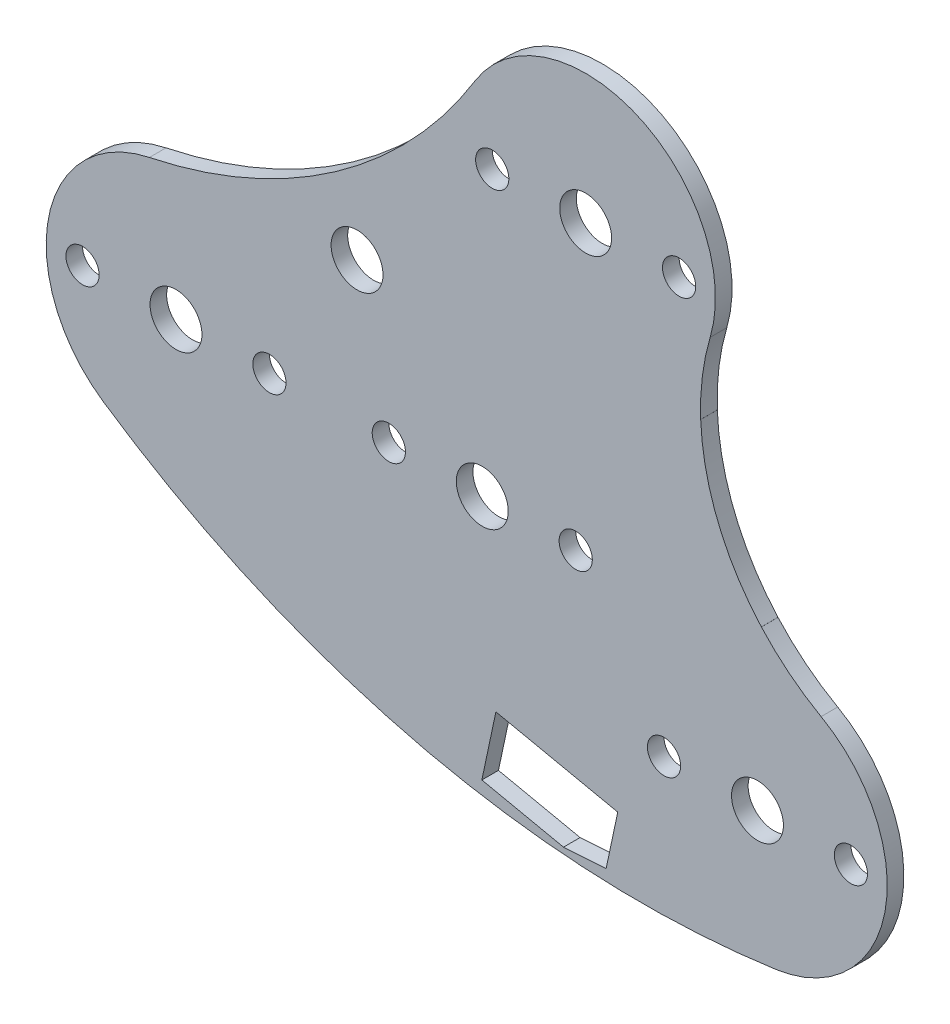
SolidWorks part; units mm, degrees
ref_plane "Front Plane" through (0, 0, 0) normal (0, 0, 1) x (1, 0, 0)
ref_plane "Top Plane" through (0, 0, 0) normal (0, 1, 0) x (1, 0, 0)
ref_plane "Right Plane" through (0, 0, 0) normal (1, 0, 0) x (0, 0, -1)
sketch "Sketch1" plane through (0, 0, 0) normal (0, 0, 1) x (1, 0, 0)
  line L0 (157.8919, 26.2701) -> (191.7747, 29.0915)
  line L1 (157.8919, 26.2701) -> (191.7747, 26.2701)
  line L2 (157.8919, 26.2701) -> (157.8919, 29.0915)
  line L3 (157.8919, 29.0915) -> (191.7747, 29.0915)
  line L4 (191.7747, 26.2701) -> (191.7747, 29.0915)
  line L5 (123.8919, 26.2701) -> (90.0092, 26.2701)
  line L6 (123.8919, 26.2701) -> (123.8919, 29.0915)
  line L7 (123.8919, 29.0915) -> (90.0092, 29.0915)
  line L8 (90.0092, 26.2701) -> (90.0092, 29.0915)
  line L9 (90.0092, 29.0915) -> (123.8919, 26.2701)
  line L10 (168.0919, 58.3601) -> (194.8735, 70.7292)
  line L11 (168.0919, 58.3601) -> (194.8735, 58.3601)
  line L12 (168.0919, 58.3601) -> (168.0919, 70.7292)
  line L13 (168.0919, 70.7292) -> (194.8735, 70.7292)
  line L14 (194.8735, 58.3601) -> (194.8735, 70.7292)
  line L15 (194.8735, 70.7292) -> (224.3587, 70.7292)
  line L16 (194.8735, 70.7292) -> (194.8735, 69.7923)
  line L17 (194.8735, 69.7923) -> (224.3587, 69.7923)
  line L18 (224.3587, 70.7292) -> (224.3587, 69.7923)
  line L19 (224.3587, 69.7923) -> (253.5106, 69.7923)
  line L20 (224.3587, 69.7923) -> (224.3587, 65.2742)
  line L21 (224.3587, 65.2742) -> (253.5106, 65.2742)
  line L22 (253.5106, 69.7923) -> (253.5106, 65.2742)
  line L23 (224.3587, 69.7923) -> (194.8735, 70.7292)
  line L24 (253.5106, 65.2742) -> (224.3587, 69.7923)
  line L25 (170.7502, 87.7401) -> (168.0919, 58.3601)
  line L26 (168.0919, 58.3601) -> (170.7502, 58.3601)
  line L27 (168.0919, 58.3601) -> (168.0919, 87.7401)
  line L28 (168.0919, 87.7401) -> (170.7502, 87.7401)
  line L29 (170.7502, 58.3601) -> (170.7502, 87.7401)
  line L30 (52.9966, 89.4705) -> (24.4119, 82.1791)
  line L31 (24.4119, 82.1791) -> (52.9966, 82.1791)
  line L32 (24.4119, 82.1791) -> (24.4119, 89.4705)
  line L33 (24.4119, 89.4705) -> (52.9966, 89.4705)
  line L34 (52.9966, 82.1791) -> (52.9966, 89.4705)
  line L35 (82.4966, 89.4705) -> (109.0019, 89.4705)
  line L36 (82.4966, 89.4705) -> (82.4966, 76.5201)
  line L37 (82.4966, 76.5201) -> (109.0019, 76.5201)
  line L38 (109.0019, 89.4705) -> (109.0019, 76.5201)
  line L39 (92.4554, 117.2387) -> (82.4966, 117.2387)
  line L40 (92.4554, 117.2387) -> (92.4554, 89.4705)
  line L41 (92.4554, 89.4705) -> (82.4966, 89.4705)
  line L42 (82.4966, 117.2387) -> (82.4966, 89.4705)
  line L43 (92.4554, 117.2387) -> (82.4966, 89.4705)
  line L44 (109.0019, 76.5201) -> (82.4966, 89.4705)
  circle A0 centre (123.8919, 26.2701) radius 14.25
  circle A1 centre (157.8919, 26.2701) radius 14.25
  circle A2 centre (90.0092, 29.0915) radius 14.25
  circle A3 centre (191.7747, 29.0915) radius 14.25
  circle A4 centre (82.4966, 89.4705) radius 11.25
  circle A5 centre (92.4554, 117.2387) radius 11.25
  circle A6 centre (52.9966, 89.4705) radius 11.25
  circle A7 centre (109.0019, 76.5201) radius 11.25
  circle A8 centre (24.4119, 82.1791) radius 11.25
  circle A9 centre (170.7502, 87.7401) radius 11.25
  circle A10 centre (168.0919, 58.3601) radius 11.25
  circle A11 centre (197.5318, 100.1092) radius 11.25
  circle A12 centre (194.8735, 70.7292) radius 11.25
  circle A13 centre (227.0169, 99.1723) radius 11.25
  circle A14 centre (224.3587, 69.7923) radius 11.25
  circle A15 centre (256.1689, 94.6541) radius 11.25
  circle A16 centre (253.5106, 65.2742) radius 11.25
  circle A17 centre (24.4119, 82.1791) radius 12
  circle A18 centre (52.9966, 89.4705) radius 12
  circle A19 centre (92.4554, 117.2387) radius 12
  circle A20 centre (82.4966, 89.4705) radius 12
  circle A21 centre (109.0019, 76.5201) radius 12
  circle A22 centre (168.0919, 58.3601) radius 12
  circle A23 centre (194.8735, 70.7292) radius 12
  circle A24 centre (224.3587, 69.7923) radius 12
  circle A25 centre (253.5106, 65.2742) radius 12
  circle A26 centre (256.1689, 94.6541) radius 12
  circle A27 centre (227.0169, 99.1723) radius 12
  circle A28 centre (197.5318, 100.1092) radius 12
  circle A29 centre (170.7502, 87.7401) radius 12
  circle A30 centre (191.7747, 29.0915) radius 15
  circle A31 centre (157.8919, 26.2701) radius 15
  circle A32 centre (123.8919, 26.2701) radius 15
  circle A33 centre (90.0092, 29.0915) radius 15
  circle A34 centre (173.429, 117.1182) radius 11.25
  circle A35 centre (173.429, 117.1182) radius 12
  dimension "D1" = 28.5
  dimension "D2" = 22.5
  dimension "D3" = 0.75
  dimension "D4" = 0.75
  dimension "D34" = 34
  dimension "D5" = 29.5
  dimension "D6" = 29.5
  dimension "D7" = 29.5
  dimension "D8" = 29.5
  dimension "D9" = 29.5
  dimension "D10" = 29.5
  dimension "D11" = 29.5
  dimension "D12" = 29.5
  dimension "D13" = 29.5
  dimension "D14" = 29.5
  dimension "D15" = 29.5
  dimension "D16" = 29.5
  dimension "D17" = 29.5
  dimension "D18" = 29.5
  dimension "D19" = 34
  dimension "D20" = 34
  dimension "D21" = 32.09
  dimension "D22" = 10.2
  dimension "D23" = 4.76
  dimension "D24" = 4.76
  dimension "D25" = 24.79
  dimension "D26" = 1.82
  dimension "D27" = 8.81
  dimension "D28" = 84.83
  dimension "D29" = 75.69
  dimension "D30" = 70.27
  dimension "D31" = 26.04
  dimension "D32" = 14.89
  dimension "D33" = 50.25
  dimension "D35" = 29.5
  dimension "D36" = 29.5
sketch "Sketch4" plane through (-30.2083, 20.075, 0) normal (0, 0, 1) x (0.9781, -0.2079, 0)
  line L0 (86.1706, 94.1917) -> (105.2206, 75.1417)
  line L1 (67.1206, 94.1917) -> (86.1706, 94.1917)
  line L2 (67.1206, 94.1917) -> (67.1206, 75.1417)
  line L3 (67.1206, 75.1417) -> (86.1706, 75.1417)
  line L4 (86.1706, 94.1917) -> (86.1706, 75.1417)
  line L5 (86.1706, 94.1917) -> (105.2206, 94.1917)
  line L6 (86.1706, 94.1917) -> (86.1706, 75.1417)
  line L7 (86.1706, 75.1417) -> (105.2206, 75.1417)
  line L8 (105.2206, 94.1917) -> (105.2206, 75.1417)
  line L9 (105.2206, 94.1917) -> (124.2706, 94.1917)
  line L10 (105.2206, 94.1917) -> (105.2206, 75.1417)
  line L11 (105.2206, 75.1417) -> (124.2706, 75.1417)
  line L12 (124.2706, 94.1917) -> (124.2706, 75.1417)
  line L13 (86.1706, 94.1917) -> (105.2206, 94.1917)
  line L14 (86.1706, 94.1917) -> (86.1706, 113.2417)
  line L15 (86.1706, 113.2417) -> (105.2206, 113.2417)
  line L16 (105.2206, 94.1917) -> (105.2206, 113.2417)
  line L17 (66.9585, 85.1784) -> (124.4326, 84.1551)
  point P14 (95.6956, 84.6667)
  point P15 (95.6956, 84.6667)
  dimension "D1" = 19.05
sketch "Sketch9" plane through (0, 0, 0) normal (0, 0, 1) x (1, 0, 0)
  line L1 (17.3619, 89.2291) -> (31.4619, 89.2291)
  line L2 (17.3619, 89.2291) -> (17.3619, 75.1291)
  line L3 (17.3619, 75.1291) -> (31.4619, 75.1291)
  line L4 (31.4619, 89.2291) -> (31.4619, 75.1291)
  line L5 (45.9466, 96.5205) -> (60.0466, 96.5205)
  line L6 (45.9466, 96.5205) -> (45.9466, 82.4205)
  line L7 (45.9466, 82.4205) -> (60.0466, 82.4205)
  line L8 (60.0466, 96.5205) -> (60.0466, 82.4205)
  line L9 (75.4466, 96.5205) -> (89.5466, 96.5205)
  line L10 (75.4466, 96.5205) -> (75.4466, 82.4205)
  line L11 (75.4466, 82.4205) -> (89.5466, 82.4205)
  line L12 (89.5466, 96.5205) -> (89.5466, 82.4205)
  line L13 (101.9519, 83.5701) -> (116.0519, 83.5701)
  line L14 (101.9519, 83.5701) -> (101.9519, 69.4701)
  line L15 (101.9519, 69.4701) -> (116.0519, 69.4701)
  line L16 (116.0519, 83.5701) -> (116.0519, 69.4701)
  line L17 (85.4054, 124.2887) -> (99.5054, 124.2887)
  line L18 (85.4054, 124.2887) -> (85.4054, 110.1887)
  line L19 (85.4054, 110.1887) -> (99.5054, 110.1887)
  line L20 (99.5054, 124.2887) -> (99.5054, 110.1887)
  line L21 (82.9592, 36.1415) -> (97.0592, 36.1415)
  line L22 (82.9592, 36.1415) -> (82.9592, 22.0415)
  line L23 (82.9592, 22.0415) -> (97.0592, 22.0415)
  line L24 (97.0592, 36.1415) -> (97.0592, 22.0415)
  line L25 (116.8419, 33.3201) -> (130.9419, 33.3201)
  line L26 (116.8419, 33.3201) -> (116.8419, 19.2201)
  line L27 (116.8419, 19.2201) -> (130.9419, 19.2201)
  line L28 (130.9419, 33.3201) -> (130.9419, 19.2201)
  line L29 (150.8419, 33.3201) -> (164.9419, 33.3201)
  line L30 (150.8419, 33.3201) -> (150.8419, 19.2201)
  line L31 (150.8419, 19.2201) -> (164.9419, 19.2201)
  line L32 (164.9419, 33.3201) -> (164.9419, 19.2201)
  line L33 (184.7247, 36.1415) -> (198.8247, 36.1415)
  line L34 (184.7247, 36.1415) -> (184.7247, 22.0415)
  line L35 (184.7247, 22.0415) -> (198.8247, 22.0415)
  line L36 (198.8247, 36.1415) -> (198.8247, 22.0415)
  line L37 (260.5606, 58.2242) -> (246.4606, 58.2242)
  line L38 (260.5606, 58.2242) -> (260.5606, 72.3242)
  line L39 (260.5606, 72.3242) -> (246.4606, 72.3242)
  line L40 (246.4606, 58.2242) -> (246.4606, 72.3242)
  line L41 (217.3087, 76.8423) -> (231.4087, 76.8423)
  line L42 (217.3087, 76.8423) -> (217.3087, 62.7423)
  line L43 (217.3087, 62.7423) -> (231.4087, 62.7423)
  line L44 (231.4087, 76.8423) -> (231.4087, 62.7423)
  line L45 (187.8235, 77.7792) -> (201.9235, 77.7792)
  line L46 (187.8235, 77.7792) -> (187.8235, 63.6792)
  line L47 (187.8235, 63.6792) -> (201.9235, 63.6792)
  line L48 (201.9235, 77.7792) -> (201.9235, 63.6792)
  line L49 (161.0419, 65.4101) -> (175.1419, 65.4101)
  line L50 (161.0419, 65.4101) -> (161.0419, 51.3101)
  line L51 (161.0419, 51.3101) -> (175.1419, 51.3101)
  line L52 (175.1419, 65.4101) -> (175.1419, 51.3101)
  line L53 (163.7002, 94.7901) -> (177.8002, 94.7901)
  line L54 (163.7002, 94.7901) -> (163.7002, 80.6901)
  line L55 (163.7002, 80.6901) -> (177.8002, 80.6901)
  line L56 (177.8002, 94.7901) -> (177.8002, 80.6901)
  line L57 (190.4818, 107.1592) -> (204.5818, 107.1592)
  line L58 (190.4818, 107.1592) -> (190.4818, 93.0592)
  line L59 (190.4818, 93.0592) -> (204.5818, 93.0592)
  line L60 (204.5818, 107.1592) -> (204.5818, 93.0592)
  line L61 (219.9669, 106.2223) -> (234.0669, 106.2223)
  line L62 (219.9669, 106.2223) -> (219.9669, 92.1223)
  line L63 (219.9669, 92.1223) -> (234.0669, 92.1223)
  line L64 (234.0669, 106.2223) -> (234.0669, 92.1223)
  line L65 (249.1189, 101.7041) -> (263.2189, 101.7041)
  line L66 (249.1189, 101.7041) -> (249.1189, 87.6041)
  line L67 (249.1189, 87.6041) -> (263.2189, 87.6041)
  line L68 (263.2189, 101.7041) -> (263.2189, 87.6041)
  line L69 (166.379, 124.1682) -> (180.479, 124.1682)
  line L70 (166.379, 124.1682) -> (166.379, 110.0682)
  line L71 (166.379, 110.0682) -> (180.479, 110.0682)
  line L72 (180.479, 124.1682) -> (180.479, 110.0682)
  point P72 (24.4119, 89.2291)
  point P74 (52.9966, 96.5205)
  point P76 (82.4966, 96.5205)
  point P78 (92.4554, 124.2887)
  point P80 (109.0019, 83.5701)
  point P82 (90.0092, 36.1415)
  point P84 (123.8919, 33.3201)
  point P86 (157.8919, 33.3201)
  point P88 (191.7747, 36.1415)
  point P90 (168.0919, 65.4101)
  point P92 (170.7502, 94.7901)
  point P94 (173.429, 124.1682)
  point P96 (197.5318, 107.1592)
  point P98 (227.0169, 106.2223)
  point P100 (256.1689, 101.7041)
  point P102 (194.8735, 77.7792)
  point P104 (224.3587, 76.8423)
  point P106 (253.5106, 72.3242)
  point P108 (17.3619, 82.1791)
  point P109 (45.9466, 89.4705)
  point P110 (75.4466, 89.4705)
  point P111 (101.9519, 76.5201)
  point P112 (85.4054, 117.2387)
  point P113 (82.9592, 29.0915)
  point P114 (116.8419, 26.2701)
  point P115 (150.8419, 26.2701)
  point P116 (184.7247, 29.0915)
  point P118 (161.0419, 58.3601)
  point P119 (187.8235, 70.7292)
  point P120 (217.3087, 69.7923)
  point P121 (246.4606, 65.2742)
  point P122 (163.7002, 87.7401)
  point P123 (190.4818, 100.1092)
  point P124 (219.9669, 99.1723)
  point P125 (249.1189, 94.6541)
  point P126 (166.379, 117.1182)
  dimension "D1" = 14.1
sketch "Sketch10" plane through (-22.0981, 19.3454, 0) normal (0, 0, 1) x (0.9781, -0.2079, 0)
  line L1 (61.5108, 90.7441) -> (75.6108, 90.7441)
  line L2 (61.5108, 90.7441) -> (61.5108, 76.6441)
  line L3 (61.5108, 76.6441) -> (75.6108, 76.6441)
  line L4 (75.6108, 90.7441) -> (75.6108, 76.6441)
  line L5 (80.5608, 90.7441) -> (94.6608, 90.7441)
  line L6 (80.5608, 90.7441) -> (80.5608, 76.6441)
  line L7 (80.5608, 76.6441) -> (94.6608, 76.6441)
  line L8 (94.6608, 90.7441) -> (94.6608, 76.6441)
  line L9 (99.6108, 90.7441) -> (113.7108, 90.7441)
  line L10 (99.6108, 90.7441) -> (99.6108, 76.6441)
  line L11 (99.6108, 76.6441) -> (113.7108, 76.6441)
  line L12 (113.7108, 90.7441) -> (113.7108, 76.6441)
  line L13 (80.5608, 109.7941) -> (94.6608, 109.7941)
  line L14 (80.5608, 109.7941) -> (80.5608, 95.6941)
  line L15 (80.5608, 95.6941) -> (94.6608, 95.6941)
  line L16 (94.6608, 109.7941) -> (94.6608, 95.6941)
  line L17 (50.5121, 89.6359) -> (53.4436, 75.8441) construction
  line L18 (59.0358, 93.2191) -> (78.0858, 93.2191) construction
  line L19 (78.0858, 112.2691) -> (97.1358, 112.2691) construction
  line L20 (97.1358, 93.2191) -> (116.1858, 93.2191) construction
  line L21 (78.0858, 93.2191) -> (78.0858, 112.2691) construction
  line L23 (59.0358, 93.2191) -> (59.0358, 74.1691) construction
  point P16 (75.6108, 83.6941)
  point P17 (94.6608, 83.6941)
  point P18 (113.7108, 83.6941)
  point P19 (87.6108, 90.7441)
  point P20 (87.6108, 109.7941)
  point P23 (68.5608, 90.7441)
  point P26 (68.5608, 93.2191)
  point P29 (87.6108, 112.2691)
  point P30 (106.6608, 90.7441)
  point P33 (106.6608, 93.2191)
  point P34 (80.5608, 102.7441)
  point P37 (78.0858, 102.7441)
  point P42 (59.0358, 83.6941)
  point P43 (61.5108, 83.6941)
sketch "Sketch14" plane through (0, 0, 0) normal (0, 0, 1) x (1, 0, 0)
  line L0 (165.1144, 80.6901) -> (163.7002, 82.1043)
  line L1 (163.7002, 93.3758) -> (165.1144, 94.7901)
  line L2 (177.8002, 93.3758) -> (176.386, 94.7901)
  line L3 (179.0648, 110.0682) -> (180.479, 111.4824)
  line L4 (166.379, 111.4824) -> (167.7932, 110.0682)
  line L5 (166.379, 122.754) -> (167.7932, 124.1682)
  line L6 (179.0648, 124.1682) -> (180.479, 122.754)
  line L7 (203.1676, 93.0592) -> (204.5818, 94.4734)
  line L8 (17.3619, 89.2291) -> (17.3619, 75.1291) construction
  line L9 (17.3619, 89.2291) -> (31.4619, 89.2291) construction
  line L10 (17.3619, 87.8149) -> (18.7761, 89.2291)
  line L11 (17.3619, 75.1291) -> (31.4619, 75.1291) construction
  line L12 (31.4619, 89.2291) -> (31.4619, 75.1291) construction
  line L13 (45.9466, 96.5205) -> (60.0466, 96.5205) construction
  line L14 (60.0466, 96.5205) -> (60.0466, 82.4205) construction
  line L15 (45.9466, 96.5205) -> (45.9466, 82.4205) construction
  line L16 (45.9466, 82.4205) -> (60.0466, 82.4205) construction
  line L17 (85.4054, 124.2887) -> (85.4054, 110.1887) construction
  line L18 (85.4054, 124.2887) -> (99.5054, 124.2887) construction
  line L19 (99.5054, 124.2887) -> (99.5054, 110.1887) construction
  line L20 (85.4054, 110.1887) -> (99.5054, 110.1887) construction
  line L21 (101.9519, 83.5701) -> (101.9519, 69.4701) construction
  line L22 (101.9519, 83.5701) -> (116.0519, 83.5701) construction
  line L23 (116.0519, 83.5701) -> (116.0519, 69.4701) construction
  line L24 (101.9519, 69.4701) -> (116.0519, 69.4701) construction
  line L25 (91.2712, 73.6044) -> (105.0631, 70.6729) construction
  line L26 (107.9947, 84.4647) -> (105.0631, 70.6729) construction
  line L27 (94.2028, 87.3963) -> (107.9947, 84.4647) construction
  line L28 (94.2028, 87.3963) -> (91.2712, 73.6044) construction
  line L29 (72.6375, 77.5651) -> (86.4294, 74.6336) construction
  line L30 (89.361, 88.4255) -> (86.4294, 74.6336) construction
  line L31 (75.5691, 91.357) -> (89.361, 88.4255) construction
  line L32 (75.5691, 91.357) -> (72.6375, 77.5651) construction
  line L33 (56.9354, 95.3177) -> (54.0038, 81.5259) construction
  line L34 (56.9354, 95.3177) -> (70.7273, 92.3862) construction
  line L35 (70.7273, 92.3862) -> (67.7957, 78.5943) construction
  line L36 (54.0038, 81.5259) -> (67.7957, 78.5943) construction
  line L37 (76.5983, 96.1988) -> (90.3901, 93.2673) construction
  line L38 (93.3217, 107.0592) -> (90.3901, 93.2673) construction
  line L39 (79.5298, 109.9907) -> (76.5983, 96.1988) construction
  line L40 (79.5298, 109.9907) -> (93.3217, 107.0592) construction
  line L41 (82.9592, 36.1415) -> (82.9592, 22.0415) construction
  line L42 (82.9592, 36.1415) -> (97.0592, 36.1415) construction
  line L43 (82.9592, 22.0415) -> (97.0592, 22.0415) construction
  line L44 (97.0592, 36.1415) -> (97.0592, 22.0415) construction
  line L45 (116.8419, 33.3201) -> (116.8419, 19.2201) construction
  line L46 (116.8419, 33.3201) -> (130.9419, 33.3201) construction
  line L47 (116.8419, 19.2201) -> (130.9419, 19.2201) construction
  line L48 (130.9419, 33.3201) -> (130.9419, 19.2201) construction
  line L49 (150.8419, 33.3201) -> (150.8419, 19.2201) construction
  line L50 (150.8419, 33.3201) -> (164.9419, 33.3201) construction
  line L51 (164.9419, 33.3201) -> (164.9419, 19.2201) construction
  line L52 (150.8419, 19.2201) -> (164.9419, 19.2201) construction
  line L53 (184.7247, 36.1415) -> (184.7247, 22.0415) construction
  line L54 (184.7247, 22.0415) -> (198.8247, 22.0415) construction
  line L55 (198.8247, 36.1415) -> (198.8247, 22.0415) construction
  line L56 (184.7247, 36.1415) -> (198.8247, 36.1415) construction
  line L57 (161.0419, 65.4101) -> (175.1419, 65.4101) construction
  line L58 (175.1419, 65.4101) -> (175.1419, 51.3101) construction
  line L59 (161.0419, 51.3101) -> (175.1419, 51.3101) construction
  line L60 (161.0419, 65.4101) -> (161.0419, 51.3101) construction
  line L61 (187.8235, 77.7792) -> (187.8235, 63.6792) construction
  line L62 (187.8235, 77.7792) -> (201.9235, 77.7792) construction
  line L63 (187.8235, 63.6792) -> (201.9235, 63.6792) construction
  line L64 (201.9235, 77.7792) -> (201.9235, 63.6792) construction
  line L65 (217.3087, 76.8423) -> (217.3087, 62.7423) construction
  line L66 (217.3087, 76.8423) -> (231.4087, 76.8423) construction
  line L67 (231.4087, 76.8423) -> (231.4087, 62.7423) construction
  line L68 (217.3087, 62.7423) -> (231.4087, 62.7423) construction
  line L69 (260.5606, 58.2242) -> (246.4606, 58.2242) construction
  line L70 (260.5606, 58.2242) -> (260.5606, 72.3242) construction
  line L71 (246.4606, 58.2242) -> (246.4606, 72.3242) construction
  line L72 (260.5606, 72.3242) -> (246.4606, 72.3242) construction
  line L73 (249.1189, 101.7041) -> (263.2189, 101.7041) construction
  line L74 (263.2189, 101.7041) -> (263.2189, 87.6041) construction
  line L75 (249.1189, 87.6041) -> (263.2189, 87.6041) construction
  line L76 (249.1189, 101.7041) -> (249.1189, 87.6041) construction
  line L77 (219.9669, 106.2223) -> (219.9669, 92.1223) construction
  line L78 (219.9669, 106.2223) -> (234.0669, 106.2223) construction
  line L79 (234.0669, 106.2223) -> (234.0669, 92.1223) construction
  line L80 (219.9669, 92.1223) -> (234.0669, 92.1223) construction
  line L81 (190.4818, 107.1592) -> (204.5818, 107.1592) construction
  line L82 (204.5818, 107.1592) -> (204.5818, 93.0592) construction
  line L83 (190.4818, 93.0592) -> (204.5818, 93.0592) construction
  line L84 (190.4818, 107.1592) -> (190.4818, 93.0592) construction
  line L85 (163.7002, 94.7901) -> (177.8002, 94.7901) construction
  line L86 (177.8002, 94.7901) -> (177.8002, 80.6901) construction
  line L87 (163.7002, 80.6901) -> (177.8002, 80.6901) construction
  line L88 (163.7002, 94.7901) -> (163.7002, 80.6901) construction
  line L89 (180.479, 124.1682) -> (180.479, 110.0682) construction
  line L90 (166.379, 110.0682) -> (180.479, 110.0682) construction
  line L91 (166.379, 124.1682) -> (166.379, 110.0682) construction
  line L92 (166.379, 124.1682) -> (180.479, 124.1682) construction
  line L93 (17.3619, 76.5433) -> (18.7761, 75.1291)
  line L94 (30.0477, 75.1291) -> (31.4619, 76.5433)
  line L95 (31.4619, 87.8149) -> (30.0477, 89.2291)
  line L96 (45.9466, 95.1063) -> (47.3608, 96.5205)
  line L97 (45.9466, 83.8347) -> (47.3608, 82.4205)
  line L98 (54.2979, 82.9092) -> (55.3871, 81.2318)
  line L99 (58.6323, 82.4205) -> (60.0466, 83.8347)
  line L100 (56.6413, 93.9344) -> (58.3187, 95.0237)
  line L101 (58.6323, 96.5205) -> (60.0466, 95.1063)
  line L102 (69.3439, 92.6802) -> (70.4332, 91.0029)
  line L103 (68.0897, 79.9776) -> (66.4124, 78.8883)
  line L104 (75.2751, 89.9737) -> (76.9524, 91.063)
  line L105 (72.9316, 78.9484) -> (74.0208, 77.2711)
  line L106 (85.0461, 74.9276) -> (86.7234, 76.0169)
  line L107 (89.0669, 87.0421) -> (87.9777, 88.7195)
  line L108 (89.0068, 93.5613) -> (90.6842, 94.6506)
  line L109 (76.8923, 97.5822) -> (77.9816, 95.9048)
  line L110 (91.9384, 107.3532) -> (93.0277, 105.6759)
  line L111 (79.2358, 108.6074) -> (80.9131, 109.6967)
  line L112 (85.4054, 111.6029) -> (86.8196, 110.1887)
  line L113 (98.0912, 110.1887) -> (99.5054, 111.6029)
  line L114 (98.0912, 124.2887) -> (99.5054, 122.8745)
  line L115 (85.4054, 122.8745) -> (86.8196, 124.2887)
  line L116 (93.9088, 86.013) -> (95.5861, 87.1023)
  line L117 (91.5653, 74.9877) -> (92.6546, 73.3104)
  line L118 (103.6798, 70.9669) -> (105.3572, 72.0562)
  line L119 (106.6114, 84.7588) -> (107.7006, 83.0814)
  line L120 (101.9519, 82.1559) -> (103.3662, 83.5701)
  line L121 (101.9519, 70.8843) -> (103.3662, 69.4701)
  line L122 (114.6377, 69.4701) -> (116.0519, 70.8843)
  line L123 (116.0519, 82.1559) -> (114.6377, 83.5701)
  line L124 (82.9592, 34.7272) -> (84.3734, 36.1415)
  line L125 (82.9592, 23.4557) -> (84.3734, 22.0415)
  line L126 (95.645, 22.0415) -> (97.0592, 23.4557)
  line L127 (97.0592, 34.7272) -> (95.645, 36.1415)
  line L128 (116.8419, 31.9059) -> (118.2562, 33.3201)
  line L129 (116.8419, 20.6343) -> (118.2562, 19.2201)
  line L130 (129.5277, 19.2201) -> (130.9419, 20.6343)
  line L131 (130.9419, 31.9059) -> (129.5277, 33.3201)
  line L132 (150.8419, 31.9059) -> (152.2562, 33.3201)
  line L133 (150.8419, 20.6343) -> (152.2562, 19.2201)
  line L134 (163.5277, 19.2201) -> (164.9419, 20.6343)
  line L135 (164.9419, 31.9059) -> (163.5277, 33.3201)
  line L136 (184.7247, 34.7272) -> (186.1389, 36.1415)
  line L137 (184.7247, 23.4557) -> (186.1389, 22.0415)
  line L138 (197.4105, 22.0415) -> (198.8247, 23.4557)
  line L139 (198.8247, 34.7272) -> (197.4105, 36.1415)
  line L140 (173.7277, 51.3101) -> (175.1419, 52.7243)
  line L141 (161.0419, 52.7243) -> (162.4562, 51.3101)
  line L142 (161.0419, 63.9959) -> (162.4562, 65.4101)
  line L143 (173.7277, 65.4101) -> (175.1419, 63.9959)
  line L144 (187.8235, 65.0934) -> (189.2378, 63.6792)
  line L145 (200.5093, 63.6792) -> (201.9235, 65.0934)
  line L146 (200.5093, 77.7792) -> (201.9235, 76.365)
  line L147 (187.8235, 76.365) -> (189.2378, 77.7792)
  line L148 (176.386, 80.6901) -> (177.8002, 82.1043)
  line L149 (204.5818, 105.745) -> (203.1676, 107.1592)
  line L150 (191.896, 107.1592) -> (190.4818, 105.745)
  line L151 (190.4818, 94.4734) -> (191.896, 93.0592)
  line L152 (219.9669, 104.8081) -> (221.3812, 106.2223)
  line L153 (232.6527, 106.2223) -> (234.0669, 104.8081)
  line L154 (234.0669, 93.5365) -> (232.6527, 92.1223)
  line L155 (219.9669, 93.5365) -> (221.3812, 92.1223)
  line L156 (229.9944, 76.8423) -> (231.4087, 75.4281)
  line L157 (217.3087, 75.4281) -> (218.7229, 76.8423)
  line L158 (217.3087, 64.1565) -> (218.7229, 62.7423)
  line L159 (229.9944, 62.7423) -> (231.4087, 64.1565)
  line L160 (259.1464, 72.3242) -> (260.5606, 70.9099)
  line L161 (246.4606, 70.9099) -> (247.8748, 72.3242)
  line L162 (259.1464, 58.2242) -> (260.5606, 59.6384)
  line L163 (247.8748, 58.2242) -> (246.4606, 59.6384)
  line L164 (261.8047, 87.6041) -> (263.2189, 89.0183)
  line L165 (249.1189, 89.0183) -> (250.5331, 87.6041)
  line L166 (249.1189, 100.2899) -> (250.5331, 101.7041)
  line L167 (261.8047, 101.7041) -> (263.2189, 100.2899)
  line L168 (75.4466, 96.5205) -> (75.4466, 82.4205) construction
  line L169 (75.4466, 96.5205) -> (89.5466, 96.5205) construction
  line L170 (89.5466, 96.5205) -> (89.5466, 82.4205) construction
  line L171 (75.4466, 82.4205) -> (89.5466, 82.4205) construction
  line L172 (76.8608, 96.5205) -> (75.4466, 95.1063)
  line L173 (88.1323, 96.5205) -> (89.5466, 95.1063)
  line L174 (89.5466, 83.8347) -> (88.1323, 82.4205)
  line L175 (75.4466, 83.8347) -> (76.8608, 82.4205)
  arc A0 (17.3619, 87.8149) -> (18.7761, 89.2291) centre (18.069, 88.522) cw
  arc A1 (18.7761, 75.1291) -> (17.3619, 76.5433) centre (18.069, 75.8362) cw
  arc A2 (31.4619, 76.5433) -> (30.0477, 75.1291) centre (30.7548, 75.8362) cw
  arc A3 (30.0477, 89.2291) -> (31.4619, 87.8149) centre (30.7548, 88.522) cw
  arc A4 (58.6323, 96.5205) -> (60.0466, 95.1063) centre (59.3394, 95.8134) cw
  arc A5 (45.9466, 95.1063) -> (47.3608, 96.5205) centre (46.6537, 95.8134) cw
  arc A6 (47.3608, 82.4205) -> (45.9466, 83.8347) centre (46.6537, 83.1276) cw
  arc A7 (60.0466, 83.8347) -> (58.6323, 82.4205) centre (59.3394, 83.1276) cw
  arc A8 (85.4054, 122.8745) -> (86.8196, 124.2887) centre (86.1125, 123.5816) cw
  arc A9 (98.0912, 124.2887) -> (99.5054, 122.8745) centre (98.7983, 123.5816) cw
  arc A10 (99.5054, 111.6029) -> (98.0912, 110.1887) centre (98.7983, 110.8958) cw
  arc A11 (85.4054, 111.6029) -> (86.8196, 110.1887) centre (86.1125, 110.8958) ccw
  arc A12 (101.9519, 82.1559) -> (103.3662, 83.5701) centre (102.6591, 82.863) cw
  arc A13 (114.6377, 83.5701) -> (116.0519, 82.1559) centre (115.3448, 82.863) cw
  arc A14 (116.0519, 70.8843) -> (114.6377, 69.4701) centre (115.3448, 70.1772) cw
  arc A15 (101.9519, 70.8843) -> (103.3662, 69.4701) centre (102.6591, 70.1772) ccw
  arc A16 (103.6798, 70.9669) -> (105.3572, 72.0562) centre (104.5185, 71.5115) ccw
  arc A17 (106.6114, 84.7588) -> (107.7006, 83.0814) centre (107.156, 83.9201) cw
  arc A18 (93.9088, 86.013) -> (95.5861, 87.1023) centre (94.7474, 86.5576) cw
  arc A19 (91.5653, 74.9877) -> (92.6546, 73.3104) centre (92.1099, 74.1491) ccw
  arc A20 (85.0461, 74.9276) -> (86.7234, 76.0169) centre (85.8848, 75.4722) ccw
  arc A21 (87.9777, 88.7195) -> (89.0669, 87.0421) centre (88.5223, 87.8808) cw
  arc A22 (75.2751, 89.9737) -> (76.9524, 91.063) centre (76.1137, 90.5183) cw
  arc A23 (72.9316, 78.9484) -> (74.0208, 77.2711) centre (73.4762, 78.1098) ccw
  arc A24 (56.6413, 93.9344) -> (58.3187, 95.0237) centre (57.48, 94.4791) cw
  arc A25 (69.3439, 92.6802) -> (70.4332, 91.0029) centre (69.8886, 91.8415) cw
  arc A26 (68.0897, 79.9776) -> (66.4124, 78.8883) centre (67.2511, 79.433) cw
  arc A27 (54.2979, 82.9092) -> (55.3871, 81.2318) centre (54.8425, 82.0705) ccw
  arc A28 (89.0068, 93.5613) -> (90.6842, 94.6506) centre (89.8455, 94.106) ccw
  arc A29 (76.8923, 97.5822) -> (77.9816, 95.9048) centre (77.4369, 96.7435) ccw
  arc A30 (79.2358, 108.6074) -> (80.9131, 109.6967) centre (80.0744, 109.1521) cw
  arc A31 (91.9384, 107.3532) -> (93.0277, 105.6759) centre (92.483, 106.5145) cw
  arc A32 (82.9592, 34.7272) -> (84.3734, 36.1415) centre (83.6663, 35.4344) cw
  arc A33 (82.9592, 23.4557) -> (84.3734, 22.0415) centre (83.6663, 22.7486) ccw
  arc A34 (95.645, 22.0415) -> (97.0592, 23.4557) centre (96.3521, 22.7486) ccw
  arc A35 (95.645, 36.1415) -> (97.0592, 34.7272) centre (96.3521, 35.4344) cw
  arc A36 (116.8419, 31.9059) -> (118.2562, 33.3201) centre (117.5491, 32.613) cw
  arc A37 (116.8419, 20.6343) -> (118.2562, 19.2201) centre (117.5491, 19.9272) ccw
  arc A38 (129.5277, 19.2201) -> (130.9419, 20.6343) centre (130.2348, 19.9272) ccw
  arc A39 (129.5277, 33.3201) -> (130.9419, 31.9059) centre (130.2348, 32.613) cw
  arc A40 (150.8419, 31.9059) -> (152.2562, 33.3201) centre (151.5491, 32.613) cw
  arc A41 (163.5277, 33.3201) -> (164.9419, 31.9059) centre (164.2348, 32.613) cw
  arc A42 (164.9419, 20.6343) -> (163.5277, 19.2201) centre (164.2348, 19.9272) cw
  arc A43 (150.8419, 20.6343) -> (152.2562, 19.2201) centre (151.5491, 19.9272) ccw
  arc A44 (184.7247, 23.4557) -> (186.1389, 22.0415) centre (185.4318, 22.7486) ccw
  arc A45 (197.4105, 22.0415) -> (198.8247, 23.4557) centre (198.1176, 22.7486) ccw
  arc A46 (197.4105, 36.1415) -> (198.8247, 34.7272) centre (198.1176, 35.4344) cw
  arc A47 (184.7247, 34.7272) -> (186.1389, 36.1415) centre (185.4318, 35.4344) cw
  arc A48 (173.7277, 65.4101) -> (175.1419, 63.9959) centre (174.4348, 64.703) cw
  arc A49 (175.1419, 52.7243) -> (173.7277, 51.3101) centre (174.4348, 52.0172) cw
  arc A50 (161.0419, 52.7243) -> (162.4562, 51.3101) centre (161.7491, 52.0172) ccw
  arc A51 (161.0419, 63.9959) -> (162.4562, 65.4101) centre (161.7491, 64.703) cw
  arc A52 (187.8235, 76.365) -> (189.2378, 77.7792) centre (188.5306, 77.0721) cw
  arc A53 (187.8235, 65.0934) -> (189.2378, 63.6792) centre (188.5306, 64.3863) ccw
  arc A54 (200.5093, 63.6792) -> (201.9235, 65.0934) centre (201.2164, 64.3863) ccw
  arc A55 (200.5093, 77.7792) -> (201.9235, 76.365) centre (201.2164, 77.0721) cw
  arc A56 (217.3087, 75.4281) -> (218.7229, 76.8423) centre (218.0158, 76.1352) cw
  arc A57 (229.9944, 76.8423) -> (231.4087, 75.4281) centre (230.7016, 76.1352) cw
  arc A58 (231.4087, 64.1565) -> (229.9944, 62.7423) centre (230.7016, 63.4494) cw
  arc A59 (217.3087, 64.1565) -> (218.7229, 62.7423) centre (218.0158, 63.4494) ccw
  arc A60 (259.1464, 58.2242) -> (260.5606, 59.6384) centre (259.8535, 58.9313) ccw
  arc A61 (246.4606, 59.6384) -> (247.8748, 58.2242) centre (247.1677, 58.9313) ccw
  arc A62 (246.4606, 70.9099) -> (247.8748, 72.3242) centre (247.1677, 71.617) cw
  arc A63 (259.1464, 72.3242) -> (260.5606, 70.9099) centre (259.8535, 71.617) cw
  arc A64 (261.8047, 101.7041) -> (263.2189, 100.2899) centre (262.5118, 100.997) cw
  arc A65 (263.2189, 89.0183) -> (261.8047, 87.6041) centre (262.5118, 88.3112) cw
  arc A66 (250.5331, 87.6041) -> (249.1189, 89.0183) centre (249.826, 88.3112) cw
  arc A67 (249.1189, 100.2899) -> (250.5331, 101.7041) centre (249.826, 100.997) cw
  arc A68 (219.9669, 104.8081) -> (221.3812, 106.2223) centre (220.674, 105.5152) cw
  arc A69 (232.6527, 106.2223) -> (234.0669, 104.8081) centre (233.3598, 105.5152) cw
  arc A70 (234.0669, 93.5365) -> (232.6527, 92.1223) centre (233.3598, 92.8294) cw
  arc A71 (221.3812, 92.1223) -> (219.9669, 93.5365) centre (220.674, 92.8294) cw
  arc A72 (203.1676, 107.1592) -> (204.5818, 105.745) centre (203.8747, 106.4521) cw
  arc A73 (204.5818, 94.4734) -> (203.1676, 93.0592) centre (203.8747, 93.7663) cw
  arc A74 (191.896, 93.0592) -> (190.4818, 94.4734) centre (191.1889, 93.7663) cw
  arc A75 (190.4818, 105.745) -> (191.896, 107.1592) centre (191.1889, 106.4521) cw
  arc A76 (176.386, 94.7901) -> (177.8002, 93.3758) centre (177.0931, 94.0829) cw
  arc A77 (177.8002, 82.1043) -> (176.386, 80.6901) centre (177.0931, 81.3972) cw
  arc A78 (165.1144, 80.6901) -> (163.7002, 82.1043) centre (164.4073, 81.3972) cw
  arc A79 (163.7002, 93.3758) -> (165.1144, 94.7901) centre (164.4073, 94.0829) cw
  arc A80 (180.479, 111.4824) -> (179.0648, 110.0682) centre (179.7719, 110.7753) cw
  arc A81 (167.7932, 110.0682) -> (166.379, 111.4824) centre (167.0861, 110.7753) cw
  arc A82 (179.0648, 124.1682) -> (180.479, 122.754) centre (179.7719, 123.4611) cw
  arc A83 (166.379, 122.754) -> (167.7932, 124.1682) centre (167.0861, 123.4611) cw
  arc A84 (75.4466, 95.1063) -> (76.8608, 96.5205) centre (76.1537, 95.8134) cw
  arc A85 (88.1323, 96.5205) -> (89.5466, 95.1063) centre (88.8394, 95.8134) cw
  arc A86 (89.5466, 83.8347) -> (88.1323, 82.4205) centre (88.8394, 83.1276) cw
  arc A87 (76.8608, 82.4205) -> (75.4466, 83.8347) centre (76.1537, 83.1276) cw
  dimension "D1" = 45
  dimension "D2" = 1
  dimension "D71" = 45
  dimension "D3" = 45
  dimension "D4" = 45
  dimension "D5" = 45
  dimension "D6" = 45
  dimension "D7" = 45
  dimension "D8" = 45
  dimension "D9" = 45
  dimension "D10" = 45
  dimension "D11" = 45
  dimension "D12" = 45
  dimension "D13" = 45
  dimension "D14" = 45
  dimension "D15" = 45
  dimension "D16" = 45
  dimension "D17" = 45
  dimension "D18" = 45
  dimension "D19" = 45
  dimension "D20" = 45
  dimension "D21" = 45
  dimension "D22" = 45
  dimension "D23" = 45
  dimension "D24" = 45
  dimension "D25" = 45
  dimension "D26" = 45
  dimension "D27" = 45
  dimension "D28" = 45
  dimension "D29" = 45
  dimension "D30" = 45
  dimension "D31" = 45
  dimension "D32" = 45
  dimension "D33" = 45
  dimension "D34" = 45
  dimension "D35" = 45
  dimension "D36" = 45
  dimension "D37" = 45
  dimension "D38" = 45
  dimension "D39" = 45
  dimension "D40" = 45
  dimension "D41" = 45
  dimension "D42" = 45
  dimension "D43" = 45
  dimension "D44" = 45
  dimension "D45" = 45
  dimension "D46" = 45
  dimension "D47" = 45
  dimension "D48" = 45
  dimension "D49" = 45
  dimension "D50" = 45
  dimension "D51" = 45
  dimension "D52" = 45
  dimension "D53" = 45
  dimension "D54" = 45
  dimension "D55" = 45
  dimension "D56" = 45
  dimension "D57" = 45
  dimension "D58" = 45
  dimension "D59" = 45
  dimension "D60" = 45
  dimension "D61" = 45
  dimension "D62" = 45
  dimension "D63" = 45
  dimension "D64" = 45
  dimension "D65" = 45
  dimension "D66" = 45
  dimension "D67" = 45
  dimension "D68" = 45
  dimension "D69" = 45
  dimension "D70" = 45
  dimension "D72" = 45
  dimension "D73" = 45
  dimension "D74" = 45
  dimension "D75" = 45
  dimension "D76" = 45
  dimension "D77" = 45
  dimension "D78" = 45
  dimension "D79" = 45
  dimension "D80" = 45
  dimension "D81" = 45
  dimension "D82" = 45
  dimension "D83" = 45
  dimension "D84" = 45
  dimension "D85" = 45
  dimension "D86" = 45
  dimension "D87" = 45
  dimension "D88" = 45
  dimension "D89" = 45
sketch "Sketch16" plane through (0, 0, 0) normal (0, 0, 1) x (1, 0, 0)
  line L0 (81.0092, 30.6915) -> (99.0092, 30.6915)
  line L5 (17.3619, 89.2291) -> (17.3619, 75.1291) construction
  line L6 (81.0092, 30.6915) -> (81.0092, 27.4915)
  line L7 (17.3619, 75.1291) -> (31.4619, 75.1291) construction
  line L8 (15.4119, 83.7791) -> (33.4119, 83.7791)
  line L9 (15.4119, 83.7791) -> (15.4119, 80.5791)
  line L10 (15.4119, 80.5791) -> (33.4119, 80.5791)
  line L11 (33.4119, 83.7791) -> (33.4119, 80.5791)
  line L12 (81.0092, 27.4915) -> (99.0092, 27.4915)
  line L13 (99.0092, 30.6915) -> (99.0092, 27.4915)
  line L14 (114.8919, 27.8701) -> (132.8919, 27.8701)
  line L15 (114.8919, 27.8701) -> (114.8919, 24.6701)
  line L16 (114.8919, 24.6701) -> (132.8919, 24.6701)
  line L17 (132.8919, 27.8701) -> (132.8919, 24.6701)
  line L18 (148.8919, 27.8701) -> (166.8919, 27.8701)
  line L19 (148.8919, 27.8701) -> (148.8919, 24.6701)
  line L20 (148.8919, 24.6701) -> (166.8919, 24.6701)
  line L21 (166.8919, 27.8701) -> (166.8919, 24.6701)
  line L22 (182.7747, 30.6915) -> (200.7747, 30.6915)
  line L23 (182.7747, 30.6915) -> (182.7747, 27.4915)
  line L24 (182.7747, 27.4915) -> (200.7747, 27.4915)
  line L25 (200.7747, 30.6915) -> (200.7747, 27.4915)
  line L26 (43.9966, 91.0705) -> (61.9966, 91.0705)
  line L27 (43.9966, 91.0705) -> (43.9966, 87.8705)
  line L28 (43.9966, 87.8705) -> (61.9966, 87.8705)
  line L29 (61.9966, 91.0705) -> (61.9966, 87.8705)
  line L30 (73.4966, 91.0705) -> (91.4966, 91.0705)
  line L31 (73.4966, 91.0705) -> (73.4966, 87.8705)
  line L32 (73.4966, 87.8705) -> (91.4966, 87.8705)
  line L33 (91.4966, 91.0705) -> (91.4966, 87.8705)
  line L34 (100.0019, 78.1201) -> (118.0019, 78.1201)
  line L35 (100.0019, 78.1201) -> (100.0019, 74.9201)
  line L36 (100.0019, 74.9201) -> (118.0019, 74.9201)
  line L37 (118.0019, 78.1201) -> (118.0019, 74.9201)
  line L38 (83.4554, 118.8387) -> (101.4554, 118.8387)
  line L39 (83.4554, 118.8387) -> (83.4554, 115.6387)
  line L40 (83.4554, 115.6387) -> (101.4554, 115.6387)
  line L41 (101.4554, 118.8387) -> (101.4554, 115.6387)
  line L42 (164.429, 118.7182) -> (182.429, 118.7182)
  line L43 (164.429, 118.7182) -> (164.429, 115.5182)
  line L44 (164.429, 115.5182) -> (182.429, 115.5182)
  line L45 (182.429, 118.7182) -> (182.429, 115.5182)
  line L46 (161.7502, 89.3401) -> (179.7502, 89.3401)
  line L47 (161.7502, 89.3401) -> (161.7502, 86.1401)
  line L48 (161.7502, 86.1401) -> (179.7502, 86.1401)
  line L49 (179.7502, 89.3401) -> (179.7502, 86.1401)
  line L50 (188.5318, 101.7092) -> (206.5318, 101.7092)
  line L51 (188.5318, 101.7092) -> (188.5318, 98.5092)
  line L52 (188.5318, 98.5092) -> (206.5318, 98.5092)
  line L53 (206.5318, 101.7092) -> (206.5318, 98.5092)
  line L54 (159.0919, 59.9601) -> (177.0919, 59.9601)
  line L55 (159.0919, 59.9601) -> (159.0919, 56.7601)
  line L56 (159.0919, 56.7601) -> (177.0919, 56.7601)
  line L57 (177.0919, 59.9601) -> (177.0919, 56.7601)
  line L58 (185.8735, 72.3292) -> (203.8735, 72.3292)
  line L59 (185.8735, 72.3292) -> (185.8735, 69.1292)
  line L60 (185.8735, 69.1292) -> (203.8735, 69.1292)
  line L61 (203.8735, 72.3292) -> (203.8735, 69.1292)
  line L62 (218.0169, 100.7723) -> (236.0169, 100.7723)
  line L63 (218.0169, 100.7723) -> (218.0169, 97.5723)
  line L64 (218.0169, 97.5723) -> (236.0169, 97.5723)
  line L65 (236.0169, 100.7723) -> (236.0169, 97.5723)
  line L66 (215.3587, 71.3923) -> (233.3587, 71.3923)
  line L67 (215.3587, 71.3923) -> (215.3587, 68.1923)
  line L68 (215.3587, 68.1923) -> (233.3587, 68.1923)
  line L69 (233.3587, 71.3923) -> (233.3587, 68.1923)
  line L70 (247.1689, 96.2541) -> (265.1689, 96.2541)
  line L71 (247.1689, 96.2541) -> (247.1689, 93.0541)
  line L72 (247.1689, 93.0541) -> (265.1689, 93.0541)
  line L73 (265.1689, 96.2541) -> (265.1689, 93.0541)
  line L74 (244.5106, 66.8742) -> (262.5106, 66.8742)
  line L75 (244.5106, 66.8742) -> (244.5106, 63.6742)
  line L76 (244.5106, 63.6742) -> (262.5106, 63.6742)
  line L77 (262.5106, 66.8742) -> (262.5106, 63.6742)
  circle A0 centre (15.4119, 82.1791) radius 1.6
  circle A1 centre (33.4119, 82.1791) radius 1.6
  circle A2 centre (81.0092, 29.0915) radius 1.6
  circle A3 centre (99.0092, 29.0915) radius 1.6
  circle A4 centre (114.8919, 26.2701) radius 1.6
  circle A5 centre (132.8919, 26.2701) radius 1.6
  circle A6 centre (148.8919, 26.2701) radius 1.6
  circle A7 centre (166.8919, 26.2701) radius 1.6
  circle A8 centre (182.7747, 29.0915) radius 1.6
  circle A9 centre (200.7747, 29.0915) radius 1.6
  circle A10 centre (43.9966, 89.4705) radius 1.6
  circle A11 centre (61.9966, 89.4705) radius 1.6
  circle A12 centre (73.4966, 89.4705) radius 1.6
  circle A13 centre (91.4966, 89.4705) radius 1.6
  circle A14 centre (100.0019, 76.5201) radius 1.6
  circle A15 centre (118.0019, 76.5201) radius 1.6
  circle A16 centre (83.4554, 117.2387) radius 1.6
  circle A17 centre (101.4554, 117.2387) radius 1.6
  circle A18 centre (164.429, 117.1182) radius 1.6
  circle A19 centre (182.429, 117.1182) radius 1.6
  circle A20 centre (161.7502, 87.7401) radius 1.6
  circle A21 centre (179.7502, 87.7401) radius 1.6
  circle A22 centre (188.5318, 100.1092) radius 1.6
  circle A23 centre (206.5318, 100.1092) radius 1.6
  circle A24 centre (159.0919, 58.3601) radius 1.6
  circle A25 centre (177.0919, 58.3601) radius 1.6
  circle A26 centre (185.8735, 70.7292) radius 1.6
  circle A27 centre (203.8735, 70.7292) radius 1.6
  circle A28 centre (218.0169, 99.1723) radius 1.6
  circle A29 centre (236.0169, 99.1723) radius 1.6
  circle A30 centre (215.3587, 69.7923) radius 1.6
  circle A31 centre (233.3587, 69.7923) radius 1.6
  circle A32 centre (247.1689, 94.6541) radius 1.6
  circle A33 centre (265.1689, 94.6541) radius 1.6
  circle A34 centre (244.5106, 65.2742) radius 1.6
  circle A35 centre (262.5106, 65.2742) radius 1.6
  point P2 (24.4119, 75.1291)
  point P6 (17.3619, 82.1791)
  point P14 (24.4119, 80.5791)
  point P53 (90.0092, 30.6915)
  point P57 (123.8919, 27.8701)
  point P60 (157.8919, 27.8701)
  point P63 (191.7747, 30.6915)
  point P73 (52.9966, 91.0705)
  point P83 (82.4966, 91.0705)
  point P93 (109.0019, 78.1201)
  point P103 (92.4554, 118.8387)
  point P113 (173.429, 118.7182)
  point P123 (170.7502, 89.3401)
  point P133 (197.5318, 101.7092)
  point P143 (168.0919, 59.9601)
  point P153 (194.8735, 72.3292)
  point P163 (227.0169, 100.7723)
  point P173 (224.3587, 71.3923)
  point P183 (256.1689, 96.2541)
  point P193 (253.5106, 66.8742)
  dimension "D1" = 3.2
  dimension "D2" = 18
sketch "Sketch8" plane through (0, 0, 0) normal (0, 0, 1) x (1, 0, 0)
  line L0 (52.2844, 74.6389) -> (82.4966, 89.4705)
  line L1 (86.9403, 110.9459) -> (79.0189, 73.6784)
  line L2 (77.6235, 112.9262) -> (96.2572, 108.9655) construction
  line L3 (69.702, 75.6588) -> (88.3357, 71.6981) construction
  line L4 (53.3861, 72.3947) -> (55.5425, 73.4534)
  line L5 (99.6829, 63.2465) -> (101.1557, 61.3487)
  line L6 (103.1308, 62.8814) -> (82.4966, 89.4705)
  line L8 (73.6628, 94.2925) -> (77.6235, 112.9262) construction
  line L9 (55.029, 98.2532) -> (73.6628, 94.2925) construction
  line L13 (93.9017, 130.158) -> (94.0202, 130.4883)
  line L14 (99.5495, 128.1325) -> (99.6679, 128.4628)
  line L16 (99.4417, 62.7418) -> (100.7607, 61.0421)
  line L17 (55.5377, 72.894) -> (53.6064, 71.9459)
  line L19 (82.4966, 89.4705) -> (96.8441, 129.4755)
  circle A1 centre (57.4203, 106.4022) radius 2.5
  circle A2 centre (106.0456, 106.2134) radius 2.5
  circle A3 centre (76.7673, 63.0854) radius 2.5
  circle A4 centre (52.9966, 89.4705) radius 13
  circle A6 centre (92.4554, 117.2387) radius 13
  circle A7 centre (109.0019, 76.5201) radius 13
  circle A8 centre (82.4966, 89.4705) radius 25
  arc A10 (50.3337, 102.1949) -> (81.377, 124.0408) centre (40.5107, 149.1329) ccw
  circle A11 centre (103.1308, 62.8814) radius 2.5
  circle A12 centre (52.2844, 74.6389) radius 2.5
  circle A13 centre (96.8441, 129.4755) radius 2.5
  circle A14 centre (52.2844, 74.6389) radius 3
  circle A15 centre (103.1308, 62.8814) radius 3
  circle A16 centre (96.8441, 129.4755) radius 3
  arc A17 (104.9258, 113.5659) -> (115.3756, 87.8504) centre (126.3001, 107.2707) ccw
  arc A18 (45.7038, 78.7088) -> (110.8301, 63.6492) centre (97.7768, 155.5511) ccw
  circle A19 centre (92.4554, 117.2387) radius 15
  circle A20 centre (109.0019, 76.5201) radius 15
  circle A21 centre (52.9966, 89.4705) radius 15
  circle A22 centre (82.4966, 89.4705) radius 27
  arc A23 (44.5818, 77.0531) -> (111.1113, 61.6691) centre (97.7768, 155.5511) ccw
  arc A24 (49.924, 104.1525) -> (79.6727, 125.0873) centre (40.5107, 149.1329) ccw
  arc A25 (106.8443, 113.0008) -> (116.3562, 89.5935) centre (126.3001, 107.2707) ccw
  circle A26 centre (52.9966, 89.4705) radius 12.5
  circle A27 centre (109.0019, 76.5201) radius 12.5
  circle A28 centre (92.4554, 117.2387) radius 12.5
  circle A29 centre (82.4966, 89.4705) radius 24.5
  arc A30 (104.4462, 113.7071) -> (115.1305, 87.4146) centre (126.3001, 107.2707) ccw
  arc A31 (110.7597, 64.1443) -> (45.9842, 79.1227) centre (97.7768, 155.5511) cw
  arc A32 (50.4361, 101.7055) -> (81.8031, 123.7792) centre (40.5107, 149.1329) ccw
  circle A33 centre (52.9966, 89.4705) radius 15.5
  circle A34 centre (109.0019, 76.5201) radius 15.5
  circle A35 centre (92.4554, 117.2387) radius 15.5
  circle A36 centre (82.4966, 89.4705) radius 27.5
  arc A37 (107.3239, 112.8596) -> (116.6013, 90.0293) centre (126.3001, 107.2707) ccw
  arc A38 (111.1816, 61.1741) -> (44.3013, 76.6392) centre (97.7768, 155.5511) cw
  arc A39 (49.8216, 104.6419) -> (79.2466, 125.349) centre (40.5107, 149.1329) ccw
  circle A40 centre (106.0456, 106.2134) radius 3
  circle A41 centre (76.7673, 63.0854) radius 3
  circle A42 centre (57.4203, 106.4022) radius 3
  circle A43 centre (70.4353, 103.1572) radius 2.5
  dimension "D3" = 26
  dimension "D4" = 5
  dimension "D7" = 6
  dimension "D8" = 50
  dimension "D1" = 2
  dimension "D2" = 2
  dimension "D5" = 0.5
  dimension "D6" = 0.5
  dimension "D9" = 0.5
  dimension "D10" = 0.5
  dimension "D11" = 5
  dimension "D12" = 8
sketch "Sketch2" plane through (0, 0, 0) normal (0, 0, 1) x (1, 0, 0)
  line L0 (30.4119, 134.2387) -> (8.4119, 112.2387)
  line L1 (16.4119, 134.2387) -> (264.1689, 134.2387)
  line L2 (8.4119, 126.2387) -> (8.4119, 15.2864)
  line L3 (16.4119, 7.2864) -> (264.1689, 7.2864)
  line L4 (272.1689, 126.2387) -> (272.1689, 15.2864)
  line L5 (16.4119, 136.2387) -> (264.1689, 136.2387)
  line L6 (6.4119, 126.2387) -> (6.4119, 15.2864)
  line L7 (16.4119, 5.2864) -> (264.1689, 5.2864)
  line L8 (274.1689, 126.2387) -> (274.1689, 15.2864)
  line L9 (250.1689, 134.2387) -> (272.1689, 112.2387)
  line L10 (6.4119, 110.2387) -> (32.4119, 136.2387)
  line L11 (248.1689, 136.2387) -> (274.1689, 110.2387)
  line L12 (6.4119, 107.4103) -> (35.2403, 136.2387)
  line L13 (245.3405, 136.2387) -> (274.1689, 107.4103)
  circle A0 centre (24.4119, 82.1791) radius 12 construction
  circle A2 centre (256.1689, 94.6541) radius 12 construction
  arc A3 (264.1689, 136.2387) -> (274.1689, 126.2387) centre (264.1689, 126.2387) cw
  circle A4 centre (123.8919, 26.2701) radius 15 construction
  arc A5 (264.1689, 5.2864) -> (274.1689, 15.2864) centre (264.1689, 15.2864) ccw
  arc A6 (6.4119, 15.2864) -> (16.4119, 5.2864) centre (16.4119, 15.2864) ccw
  arc A7 (16.4119, 136.2387) -> (6.4119, 126.2387) centre (16.4119, 126.2387) ccw
  arc A8 (264.1689, 134.2387) -> (272.1689, 126.2387) centre (264.1689, 126.2387) cw
  arc A9 (264.1689, 7.2864) -> (272.1689, 15.2864) centre (264.1689, 15.2864) ccw
  arc A10 (8.4119, 15.2864) -> (16.4119, 7.2864) centre (16.4119, 15.2864) ccw
  arc A11 (16.4119, 134.2387) -> (8.4119, 126.2387) centre (16.4119, 126.2387) ccw
  circle A12 centre (92.4554, 117.2387) radius 13 construction
  point P4 (12.4119, 82.1791)
  point P5 (92.4554, 130.2387)
  point P8 (268.1689, 94.6541)
  point P14 (124.5912, 11.2864)
  point P36 (30.4119, 134.2387)
  point P39 (250.1689, 134.2387)
  dimension "D9" = 10
  dimension "D10" = 8
  dimension "D1" = 4
  dimension "D2" = 4
  dimension "D3" = 4
  dimension "D4" = 4
  dimension "D5" = 2
  dimension "D6" = 2
  dimension "D7" = 2
  dimension "D8" = 2
  dimension "D11" = 14
  dimension "D12" = 45
  dimension "D13" = 14
  dimension "D14" = 45
  dimension "D15" = 2
  dimension "D16" = 2
sketch "Sketch6" plane through (0, 0, 0) normal (0, 0, 1) x (1, 0, 0)
  line L0 (44.9119, 130.2387) -> (56.9119, 130.2387)
  line L1 (31.4119, 130.2387) -> (43.4119, 130.2387)
  line L2 (31.4119, 130.2387) -> (31.4119, 118.2387)
  line L3 (31.4119, 118.2387) -> (43.4119, 118.2387)
  line L4 (43.4119, 130.2387) -> (43.4119, 118.2387)
  line L5 (34.1619, 133.2387) -> (40.6619, 133.2387)
  line L6 (34.1619, 133.2387) -> (34.1619, 115.2387)
  line L7 (34.1619, 115.2387) -> (40.6619, 115.2387)
  line L8 (40.6619, 133.2387) -> (40.6619, 115.2387)
  line L9 (44.9119, 130.2387) -> (44.9119, 118.2387)
  line L10 (44.9119, 118.2387) -> (56.9119, 118.2387)
  line L11 (56.9119, 130.2387) -> (56.9119, 118.2387)
  line L12 (47.6619, 133.2387) -> (54.1619, 133.2387)
  line L13 (47.6619, 133.2387) -> (47.6619, 115.2387)
  line L14 (47.6619, 115.2387) -> (54.1619, 115.2387)
  line L15 (54.1619, 133.2387) -> (54.1619, 115.2387)
  line L16 (58.4119, 130.2387) -> (70.4119, 130.2387)
  line L17 (58.4119, 130.2387) -> (58.4119, 118.2387)
  line L18 (58.4119, 118.2387) -> (70.4119, 118.2387)
  line L19 (70.4119, 130.2387) -> (70.4119, 118.2387)
  line L20 (61.1619, 133.2387) -> (67.6619, 133.2387)
  line L21 (61.1619, 133.2387) -> (61.1619, 115.2387)
  line L22 (61.1619, 115.2387) -> (67.6619, 115.2387)
  line L23 (67.6619, 133.2387) -> (67.6619, 115.2387)
  line L24 (237.1689, 130.2387) -> (249.1689, 130.2387)
  line L25 (237.1689, 130.2387) -> (237.1689, 118.2387)
  line L26 (237.1689, 118.2387) -> (249.1689, 118.2387)
  line L27 (249.1689, 130.2387) -> (249.1689, 118.2387)
  line L28 (239.9189, 133.2387) -> (246.4189, 133.2387)
  line L29 (239.9189, 133.2387) -> (239.9189, 115.2387)
  line L30 (239.9189, 115.2387) -> (246.4189, 115.2387)
  line L31 (246.4189, 133.2387) -> (246.4189, 115.2387)
  line L32 (223.6689, 130.2387) -> (235.6689, 130.2387)
  line L33 (223.6689, 130.2387) -> (223.6689, 118.2387)
  line L34 (223.6689, 118.2387) -> (235.6689, 118.2387)
  line L35 (235.6689, 130.2387) -> (235.6689, 118.2387)
  line L36 (226.4189, 133.2387) -> (232.9189, 133.2387)
  line L37 (226.4189, 133.2387) -> (226.4189, 115.2387)
  line L38 (226.4189, 115.2387) -> (232.9189, 115.2387)
  line L39 (232.9189, 133.2387) -> (232.9189, 115.2387)
  line L40 (210.1689, 130.2387) -> (222.1689, 130.2387)
  line L41 (210.1689, 130.2387) -> (210.1689, 118.2387)
  line L42 (210.1689, 118.2387) -> (222.1689, 118.2387)
  line L43 (222.1689, 130.2387) -> (222.1689, 118.2387)
  line L44 (212.9189, 133.2387) -> (219.4189, 133.2387)
  line L45 (212.9189, 133.2387) -> (212.9189, 115.2387)
  line L46 (212.9189, 115.2387) -> (219.4189, 115.2387)
  line L47 (219.4189, 133.2387) -> (219.4189, 115.2387)
  line L48 (16.4119, 134.2387) -> (264.1689, 134.2387) construction
  line L49 (8.4119, 126.2387) -> (8.4119, 15.2864) construction
  line L50 (272.1689, 126.2387) -> (272.1689, 15.2864) construction
  circle A0 centre (37.4119, 124.2387) radius 3.4
  circle A1 centre (50.9119, 124.2387) radius 3.4
  circle A2 centre (64.4119, 124.2387) radius 3.4
  circle A3 centre (243.1689, 124.2387) radius 3.4
  circle A4 centre (229.6689, 124.2387) radius 3.4
  circle A5 centre (216.1689, 124.2387) radius 3.4
  point P8 (37.4119, 130.2387)
  point P9 (37.4119, 133.2387)
  point P10 (34.1619, 124.2387)
  point P11 (31.4119, 124.2387)
  point P15 (43.4119, 124.2387)
  point P43 (243.1689, 130.2387)
  point P44 (243.1689, 133.2387)
  point P45 (239.9189, 124.2387)
  point P46 (237.1689, 124.2387)
  point P50 (249.1689, 124.2387)
  dimension "D4" = 6.8
  dimension "D9" = 6.8
  dimension "D1" = 18
  dimension "D2" = 12
  dimension "D3" = 6.5
  dimension "D5" = 3
  dimension "D6" = 18
  dimension "D7" = 12
  dimension "D8" = 6.5
  dimension "D11" = 1
  dimension "D12" = 23
  dimension "D13" = 23
  dimension "D10" = 3
sketch "Sketch13" plane through (0, 0, 0) normal (0, 0, 1) x (1, 0, 0)
  line L1 (115.4554, 133.7387) -> (125.4554, 133.7387)
  line L2 (110.4554, 128.7387) -> (110.4554, 118.7387)
  line L3 (115.4554, 113.7387) -> (125.4554, 113.7387)
  line L4 (130.4554, 128.7387) -> (130.4554, 118.7387)
  line L5 (115.9854, 134.7387) -> (124.9254, 134.7387)
  line L6 (115.9854, 134.7387) -> (115.9854, 127.3887)
  line L7 (115.9854, 127.3887) -> (124.9254, 127.3887)
  line L8 (124.9254, 134.7387) -> (124.9254, 127.3887)
  line L9 (115.5354, 132.9887) -> (116.4354, 132.9887)
  line L10 (115.5354, 132.9887) -> (115.5354, 131.2887)
  line L11 (115.5354, 131.2887) -> (116.4354, 131.2887)
  line L12 (116.4354, 132.9887) -> (116.4354, 131.2887)
  line L13 (114.4554, 120.2387) -> (126.4554, 120.2387)
  line L14 (114.4554, 120.2387) -> (114.4554, 113.7387)
  line L15 (114.4554, 113.7387) -> (126.4554, 113.7387)
  line L16 (126.4554, 120.2387) -> (126.4554, 113.7387)
  line L19 (115.4554, 134.2387) -> (125.4554, 134.2387)
  line L20 (109.9554, 128.7387) -> (109.9554, 118.7387)
  line L21 (115.4554, 113.2387) -> (125.4554, 113.2387)
  line L22 (130.9554, 128.7387) -> (130.9554, 118.7387)
  line L23 (16.4119, 134.2387) -> (264.1689, 134.2387) construction
  arc A0 (125.4554, 134.2387) -> (130.9554, 128.7387) centre (125.4554, 128.7387) cw
  arc A1 (115.4554, 133.7387) -> (110.4554, 128.7387) centre (115.4554, 128.7387) ccw
  arc A2 (125.4554, 133.7387) -> (130.4554, 128.7387) centre (125.4554, 128.7387) cw
  arc A3 (125.4554, 113.7387) -> (130.4554, 118.7387) centre (125.4554, 118.7387) ccw
  arc A4 (110.4554, 118.7387) -> (115.4554, 113.7387) centre (115.4554, 118.7387) ccw
  circle A6 centre (112.9554, 123.7387) radius 2.5
  circle A7 centre (127.9554, 123.7387) radius 2.5
  arc A8 (125.4554, 113.2387) -> (130.9554, 118.7387) centre (125.4554, 118.7387) ccw
  arc A9 (109.9554, 118.7387) -> (115.4554, 113.2387) centre (115.4554, 118.7387) ccw
  arc A10 (115.4554, 134.2387) -> (109.9554, 128.7387) centre (115.4554, 128.7387) ccw
  circle A12 centre (92.4554, 117.2387) radius 15.5 construction
  point P9 (115.9854, 132.1387)
  point P13 (116.4354, 132.1387)
  point P14 (115.9854, 132.9887)
  point P15 (120.4554, 113.7387)
  point P16 (120.4554, 127.3887)
  point P17 (120.4554, 113.7387)
  point P34 (110.4554, 123.7387)
  point P41 (120.4554, 134.2387)
  point P42 (120.4554, 133.7387)
  point P43 (130.9554, 123.7387)
  point P44 (130.4554, 123.7387)
  point P53 (107.9554, 117.2387)
  dimension "D7" = 6.5
  dimension "D10" = 5
  dimension "D11" = 5
  dimension "D17" = 5.5
  dimension "D1" = 8.94
  dimension "D2" = 7.35
  dimension "D3" = 2.6
  dimension "D4" = 1.7
  dimension "D5" = 0.9
  dimension "D6" = 1
  dimension "D8" = 12
  dimension "D9" = 7.15
  dimension "D12" = 20
  dimension "D13" = 20
  dimension "D14" = 2
  dimension "D15" = 0.5
  dimension "D16" = 0.5
sketch "Sketch5" plane through (0, 0, 0) normal (0, 0, 1) x (1, 0, 0)
  line L0 (130.9554, 128.7387) -> (130.9554, 118.7387) construction
  line L1 (136.9554, 138.2387) -> (158.5554, 138.2387)
  line L2 (136.9554, 138.2387) -> (136.9554, 106.9387)
  line L3 (136.9554, 106.9387) -> (158.5554, 106.9387)
  line L4 (158.5554, 138.2387) -> (158.5554, 106.9387)
  line L5 (141.7554, 106.9387) -> (153.7554, 106.9387)
  line L6 (141.7554, 106.9387) -> (141.7554, 93.2387)
  line L7 (141.7554, 93.2387) -> (153.7554, 93.2387)
  line L8 (153.7554, 106.9387) -> (153.7554, 93.2387)
  line L9 (16.4119, 136.2387) -> (264.1689, 136.2387) construction
  line L11 (139.9804, 102.2387) -> (155.5304, 102.2387)
  line L12 (139.9804, 102.2387) -> (139.9804, 91.2387)
  line L13 (139.9804, 91.2387) -> (155.5304, 91.2387)
  line L14 (155.5304, 102.2387) -> (155.5304, 91.2387)
  point P8 (147.7554, 106.9387)
  point P9 (147.7554, 106.9387)
  point P18 (147.7554, 93.2387)
  point P19 (147.7554, 102.2387)
  dimension "D1" = 6
  dimension "D2" = 2
  dimension "D3" = 31.3
  dimension "D4" = 21.6
  dimension "D5" = 12
  dimension "D6" = 13.7
  dimension "D7" = 15.55
  dimension "D8" = 11
  dimension "D9" = 2
sketch "Sketch3" plane through (0, 0, 0) normal (0, 0, 1) x (1, 0, 0)
  line L0 (123.8919, 26.2701) -> (157.8919, 26.2701)
  line L1 (125.5419, 80.2945) -> (156.2419, 80.2945)
  line L2 (125.5419, 80.2945) -> (125.5419, 57.0345)
  line L3 (125.5419, 57.0345) -> (156.2419, 57.0345)
  line L4 (156.2419, 80.2945) -> (156.2419, 57.0345)
  line L5 (133.1419, 59.0345) -> (148.6419, 59.0345)
  line L6 (133.1419, 59.0345) -> (133.1419, 55.0345)
  line L7 (133.1419, 55.0345) -> (148.6419, 55.0345)
  line L8 (148.6419, 59.0345) -> (148.6419, 55.0345)
  line L9 (129.0199, 77.1945) -> (152.7639, 77.1945)
  line L10 (129.0199, 77.1945) -> (129.0199, 64.3305)
  line L11 (129.0199, 64.3305) -> (152.7639, 64.3305)
  line L12 (152.7639, 77.1945) -> (152.7639, 64.3305)
  line L13 (133.1419, 55.0345) -> (130.8952, 55.0345)
  line L14 (130.8919, 61.7345) -> (150.8919, 61.7345)
  line L15 (130.8919, 61.7345) -> (130.8919, 56.2345)
  line L16 (130.8919, 56.2345) -> (150.8919, 56.2345)
  line L17 (150.8919, 61.7345) -> (150.8919, 56.2345)
  line L18 (127.5419, 78.2945) -> (154.2419, 78.2945)
  line L19 (130.8919, 56.2345) -> (150.8919, 56.2345)
  line L23 (127.5419, 78.2945) -> (127.5419, 59.0345)
  line L24 (127.5419, 59.0345) -> (154.2419, 59.0345)
  line L25 (154.2419, 78.2945) -> (154.2419, 59.0345)
  line L26 (130.8952, 59.0345) -> (150.8887, 59.0345)
  line L27 (130.8952, 59.0345) -> (130.8952, 53.0345)
  line L28 (130.8952, 53.0345) -> (150.8887, 53.0345)
  line L29 (150.8887, 59.0345) -> (150.8887, 53.0345)
  line L30 (148.6419, 55.0345) -> (150.8887, 55.0345)
  line L31 (274.1689, 126.2387) -> (274.1689, 15.2864) construction
  point P16 (140.8919, 55.0345)
  point P17 (140.8919, 57.0345)
  point P18 (140.8919, 64.3305)
  point P19 (140.8919, 26.2701)
  point P24 (140.8919, 56.2345)
  point P31 (140.8919, 78.2945)
  point P33 (140.8919, 80.2945)
  point P35 (140.8919, 59.0345)
  point P36 (125.5419, 68.6645)
  point P37 (127.5419, 68.6645)
  point P39 (130.8952, 54.0345)
  point P41 (150.8919, 59.0345)
  point P46 (274.1689, 70.7625)
  point P47 (152.7639, 70.7625)
  dimension "D1" = 30.7
  dimension "D2" = 23.26
  dimension "D3" = 4
  dimension "D4" = 15.5
  dimension "D5" = 12.864
  dimension "D6" = 23.744
  dimension "D7" = 26.7
  dimension "D8" = 20
  dimension "D9" = 5.5
  dimension "D10" = 6
  dimension "D11" = 1
  dimension "D12" = 2.8
  dimension "D13" = 19.26
  dimension "D14" = 1.1
  dimension "D15" = 5
sketch "Sketch15" plane through (0, 0, 0) normal (0, 0, 1) x (1, 0, 0)
  line L0 (25.4223, 117.2283) -> (255.1585, 117.2283)
  line L1 (16.4119, 15.2864) -> (264.1689, 15.2864)
  line L2 (16.4119, 7.2864) -> (264.1689, 7.2864) construction
  line L4 (6.4119, 107.4103) -> (35.2403, 136.2387) construction
  line L5 (20.8261, 121.8245) -> (25.4223, 117.2283)
  circle A0 centre (25.4223, 117.2283) radius 2.5
  circle A1 centre (255.1585, 117.2283) radius 2.5
  circle A2 centre (264.1689, 15.2864) radius 2.5
  circle A3 centre (16.4119, 15.2864) radius 2.5
  point P8 (140.2904, 117.2283)
  point P9 (140.2904, 15.2864)
  point P12 (140.2904, 7.2864)
  dimension "D1" = 5
  dimension "D2" = 6.5
  dimension "D3" = 90
sketch "Sketch18" plane through (0, 0, 0) normal (0, 0, 1) x (1, 0, 0)
  line L0 (125.5419, 63.0854) -> (125.5419, 99.9387)
  line L1 (130.5419, 104.9387) -> (156.429, 104.9387)
  line L2 (161.429, 109.9387) -> (161.429, 128.7387)
  line L3 (166.429, 133.7387) -> (246.3049, 133.7387)
  line L6 (268.1689, 107.7283) -> (268.1689, 58.2742)
  line L7 (263.1689, 53.2742) -> (211.7747, 53.2742)
  line L8 (206.7747, 48.2742) -> (206.7747, 16.2701)
  line L9 (201.7747, 11.2701) -> (80.0092, 11.2701)
  line L10 (75.0092, 16.2701) -> (75.0092, 33.0854)
  line L11 (70.0092, 38.0854) -> (17.4119, 38.0854)
  line L12 (12.4119, 43.0854) -> (12.4119, 107.7283)
  line L15 (34.2758, 133.7387) -> (71.4119, 133.7387)
  line L16 (76.4119, 128.7387) -> (76.4119, 122.5671)
  line L17 (68.5834, 114.7387) -> (61.4119, 114.7387)
  line L18 (36.4119, 89.7387) -> (36.4119, 63.0854)
  line L19 (41.4119, 58.0854) -> (120.5419, 58.0854)
  line L20 (16.4119, 134.2387) -> (264.1689, 134.2387) construction
  line L21 (250.6585, 129.3851) -> (250.6585, 117.7283)
  line L24 (47.6619, 115.2387) -> (54.1619, 115.2387) construction
  line L25 (239.9189, 133.2387) -> (246.4189, 133.2387) construction
  line L26 (255.6585, 112.7283) -> (263.1689, 112.7283)
  line L27 (24.9223, 112.7283) -> (17.4119, 112.7283)
  line L29 (125.5419, 80.2945) -> (125.5419, 57.0345) construction
  line L30 (32.8616, 133.1529) -> (30.5081, 130.7994)
  line L31 (75.8261, 121.1529) -> (69.9977, 115.3245)
  line L32 (6.4119, 107.4103) -> (35.2403, 136.2387) construction
  line L33 (25.4223, 117.2283) -> (255.1585, 117.2283) construction
  line L35 (27.9119, 126.7387) -> (29.9223, 126.7387)
  line L36 (27.9119, 126.7387) -> (27.9119, 121.7387)
  line L37 (27.9119, 121.7387) -> (29.9223, 121.7387)
  line L40 (247.7191, 133.1529) -> (250.0727, 130.7994)
  line L41 (252.6689, 126.7387) -> (250.6585, 126.7387)
  line L42 (252.6689, 126.7387) -> (252.6689, 121.7387)
  line L43 (252.6689, 121.7387) -> (250.6585, 121.7387)
  line L44 (250.6585, 126.7387) -> (250.6585, 121.7387)
  line L45 (245.3405, 136.2387) -> (274.1689, 107.4103) construction
  line L46 (256.1689, 94.6541) -> (253.5106, 65.2742)
  line L47 (123.8919, 26.2701) -> (157.8919, 26.2701) construction
  line L48 (29.9223, 129.3851) -> (29.9223, 126.7387)
  line L49 (29.9223, 121.7387) -> (29.9223, 117.7283)
  line L50 (20.8261, 121.8245) -> (25.4223, 117.2283) construction
  line L51 (136.9554, 106.9387) -> (158.5554, 106.9387) construction
  line L52 (31.4119, 130.2387) -> (31.4119, 118.2387) construction
  line L53 (70.4119, 130.2387) -> (70.4119, 118.2387) construction
  line L54 (210.1689, 130.2387) -> (210.1689, 118.2387) construction
  line L55 (249.1689, 130.2387) -> (249.1689, 118.2387) construction
  circle A0 centre (73.9119, 124.2387) radius 2.5
  circle A1 centre (255.1585, 117.2283) radius 2.5 construction
  circle A2 centre (24.4119, 82.1791) radius 12 construction
  circle A3 centre (90.0092, 29.0915) radius 15 construction
  circle A4 centre (157.8919, 26.2701) radius 15 construction
  circle A5 centre (191.7747, 29.0915) radius 15 construction
  circle A6 centre (253.5106, 65.2742) radius 12 construction
  circle A7 centre (256.1689, 94.6541) radius 12 construction
  circle A8 centre (173.429, 117.1182) radius 12 construction
  circle A9 centre (76.7673, 63.0854) radius 3 construction
  arc A12 (61.4119, 114.7387) -> (36.4119, 89.7387) centre (61.4119, 89.7387) ccw
  arc A15 (268.1689, 58.2742) -> (263.1689, 53.2742) centre (263.1689, 58.2742) cw
  arc A16 (80.0092, 11.2701) -> (75.0092, 16.2701) centre (80.0092, 16.2701) cw
  arc A17 (206.7747, 16.2701) -> (201.7747, 11.2701) centre (201.7747, 16.2701) cw
  arc A18 (211.7747, 53.2742) -> (206.7747, 48.2742) centre (211.7747, 48.2742) ccw
  arc A19 (161.429, 128.7387) -> (166.429, 133.7387) centre (166.429, 128.7387) cw
  arc A20 (156.429, 104.9387) -> (161.429, 109.9387) centre (156.429, 109.9387) ccw
  arc A21 (125.5419, 99.9387) -> (130.5419, 104.9387) centre (130.5419, 99.9387) cw
  arc A22 (125.5419, 63.0854) -> (120.5419, 58.0854) centre (120.5419, 63.0854) cw
  arc A23 (75.0092, 33.0854) -> (70.0092, 38.0854) centre (70.0092, 33.0854) ccw
  arc A24 (36.4119, 63.0854) -> (41.4119, 58.0854) centre (41.4119, 63.0854) ccw
  arc A25 (17.4119, 38.0854) -> (12.4119, 43.0854) centre (17.4119, 43.0854) cw
  circle A33 centre (27.9119, 124.2387) radius 2.5
  arc A34 (29.9223, 117.7283) -> (24.9223, 112.7283) centre (24.9223, 117.7283) cw
  arc A35 (12.4119, 107.7283) -> (17.4119, 112.7283) centre (17.4119, 107.7283) cw
  arc A36 (268.1689, 107.7283) -> (263.1689, 112.7283) centre (263.1689, 107.7283) ccw
  circle A37 centre (25.4223, 117.2283) radius 2.5 construction
  circle A38 centre (17.4119, 43.0854) radius 2.5
  circle A39 centre (140.8919, 16.2701) radius 2.5
  circle A40 centre (130.5419, 99.9387) radius 2.5
  circle A41 centre (252.6689, 124.2387) radius 2.5
  circle A42 centre (206.6689, 124.2387) radius 2.5
  circle A43 centre (263.1689, 79.9641) radius 2.5
  arc A44 (250.6585, 117.7283) -> (255.6585, 112.7283) centre (255.6585, 117.7283) ccw
  arc A45 (32.8616, 133.1529) -> (34.2758, 133.7387) centre (34.2758, 131.7387) cw
  arc A46 (30.5081, 130.7994) -> (29.9223, 129.3851) centre (31.9223, 129.3851) ccw
  arc A47 (250.0727, 130.7994) -> (250.6585, 129.3851) centre (248.6585, 129.3851) cw
  arc A48 (247.7191, 133.1529) -> (246.3049, 133.7387) centre (246.3049, 131.7387) ccw
  circle A49 centre (28.9223, 120.7387) radius 1
  circle A50 centre (28.9223, 127.7387) radius 1
  circle A51 centre (251.6585, 127.7387) radius 1
  circle A52 centre (251.6585, 120.7387) radius 1
  arc A53 (75.8261, 121.1529) -> (76.4119, 122.5671) centre (74.4119, 122.5671) ccw
  arc A54 (69.9977, 115.3245) -> (68.5834, 114.7387) centre (68.5834, 116.7387) cw
  arc A55 (71.4119, 133.7387) -> (76.4119, 128.7387) centre (71.4119, 128.7387) cw
  point P5 (250.6585, 133.7387)
  point P6 (25.4223, 114.7283)
  point P16 (29.9223, 133.7387)
  point P18 (76.4119, 114.7387)
  point P52 (76.7673, 60.0854)
  point P67 (27.9223, 117.2283)
  point P110 (252.6585, 117.2283)
  point P111 (255.1585, 114.7283)
  point P134 (254.8397, 79.9641)
  point P142 (140.8919, 26.2701)
  point P162 (76.4119, 121.7387)
  point P165 (69.4119, 114.7387)
  dimension "D3" = 5
  dimension "D5" = 0.5
  dimension "D10" = 2
  dimension "D11" = 25
  dimension "D12" = 5
  dimension "D13" = 2
  dimension "D6" = 2
  dimension "D9" = 2
  dimension "D17" = 5
  dimension "D19" = 2
  dimension "D20" = 2
  dimension "D21" = 2
  dimension "D1" = 0.5
  dimension "D2" = 0.5
  dimension "D4" = 0.5
  dimension "D7" = 2
  dimension "D8" = 20
  dimension "D15" = 2
  dimension "D16" = 0.5
  dimension "D18" = 5
  dimension "D22" = 3.5
  dimension "D23" = 3.5
  dimension "D24" = 3.5
  dimension "D25" = 3.5
sketch "Sketch19" plane through (0, 0, 0) normal (0, 0, 1) x (1, 0, 0)
  line L0 (11.9119, 107.7283) -> (11.9119, 43.0854)
  line L1 (17.4119, 37.5854) -> (70.0092, 37.5854)
  line L2 (74.5092, 33.0854) -> (74.5092, 16.2701)
  line L3 (80.0092, 10.7701) -> (201.7747, 10.7701)
  line L4 (207.2747, 16.2701) -> (207.2747, 48.2742)
  line L5 (211.7747, 52.7742) -> (263.1689, 52.7742)
  line L6 (268.6689, 58.2742) -> (268.6689, 107.7283)
  line L7 (263.1689, 113.2283) -> (255.6585, 113.2283)
  line L9 (70.0092, 38.0854) -> (17.4119, 38.0854) construction
  line L12 (24.9223, 113.2283) -> (17.4119, 113.2283)
  line L13 (24.9223, 112.7283) -> (17.4119, 112.7283) construction
  line L14 (75.0092, 16.2701) -> (75.0092, 33.0854) construction
  line L15 (16.4119, 134.2387) -> (264.1689, 134.2387) construction
  line L16 (12.4119, 43.0854) -> (12.4119, 107.7283) construction
  line L17 (201.7747, 11.2701) -> (80.0092, 11.2701) construction
  line L18 (206.7747, 48.2742) -> (206.7747, 16.2701) construction
  line L19 (263.1689, 53.2742) -> (211.7747, 53.2742) construction
  line L20 (268.1689, 107.7283) -> (268.1689, 58.2742) construction
  line L21 (255.6585, 112.7283) -> (263.1689, 112.7283) construction
  line L22 (251.1585, 117.7283) -> (251.1585, 121.2387)
  line L23 (245.3405, 136.2387) -> (274.1689, 107.4103) construction
  line L24 (248.0727, 133.5065) -> (250.4262, 131.1529)
  line L25 (246.3049, 134.2387) -> (166.429, 134.2387)
  line L26 (250.6585, 129.3851) -> (250.6585, 117.7283) construction
  line L27 (251.1585, 129.3851) -> (251.1585, 127.2387)
  line L28 (251.1585, 127.2387) -> (252.6689, 127.2387)
  line L29 (251.1585, 121.2387) -> (252.6689, 121.2387)
  line L30 (252.6689, 121.7387) -> (250.6585, 121.7387) construction
  line L31 (252.6689, 126.7387) -> (250.6585, 126.7387) construction
  line L32 (160.929, 128.7387) -> (160.929, 109.9387)
  line L33 (156.429, 105.4387) -> (130.5419, 105.4387)
  line L34 (125.0419, 99.9387) -> (125.0419, 63.0854)
  line L35 (120.5419, 58.5854) -> (41.4119, 58.5854)
  line L36 (36.9119, 63.0854) -> (36.9119, 89.7387)
  line L37 (61.4119, 114.2387) -> (68.5834, 114.2387)
  line L38 (76.9119, 122.5671) -> (76.9119, 128.7387)
  line L39 (71.4119, 134.2387) -> (34.2758, 134.2387)
  line L40 (76.4119, 128.7387) -> (76.4119, 122.5671) construction
  line L41 (68.5834, 114.7387) -> (61.4119, 114.7387) construction
  line L42 (70.3512, 114.9709) -> (76.1796, 120.7994)
  line L43 (32.5081, 133.5065) -> (30.1545, 131.1529)
  line L44 (75.8261, 121.1529) -> (69.9977, 115.3245) construction
  line L45 (36.4119, 89.7387) -> (36.4119, 63.0854) construction
  line L46 (41.4119, 58.0854) -> (120.5419, 58.0854) construction
  line L47 (125.5419, 63.0854) -> (125.5419, 99.9387) construction
  line L48 (130.5419, 104.9387) -> (156.429, 104.9387) construction
  line L49 (161.429, 109.9387) -> (161.429, 128.7387) construction
  line L50 (166.429, 134.2387) -> (71.4119, 134.2387)
  line L52 (6.4119, 107.4103) -> (35.2403, 136.2387) construction
  line L53 (29.4223, 117.7283) -> (29.4223, 121.2387)
  line L54 (29.4223, 129.3851) -> (29.4223, 127.2387)
  line L55 (29.9223, 129.3851) -> (29.9223, 126.7387) construction
  line L56 (27.9119, 126.7387) -> (29.9223, 126.7387) construction
  line L57 (29.4223, 127.2387) -> (27.9119, 127.2387)
  line L58 (29.4223, 121.2387) -> (27.9119, 121.2387)
  line L59 (27.9119, 121.7387) -> (29.9223, 121.7387) construction
  line L60 (252.6689, 126.7387) -> (252.6689, 121.7387) construction
  arc A0 (252.6689, 127.2387) -> (252.6689, 121.2387) centre (252.6689, 124.2387) cw
  arc A2 (251.1585, 129.3851) -> (250.4262, 131.1529) centre (248.6585, 129.3851) ccw
  arc A3 (248.0727, 133.5065) -> (246.3049, 134.2387) centre (246.3049, 131.7387) ccw
  arc A4 (251.1585, 117.7283) -> (255.6585, 113.2283) centre (255.6585, 117.7283) ccw
  arc A7 (247.7191, 133.1529) -> (246.3049, 133.7387) centre (246.3049, 131.7387) ccw construction
  arc A8 (27.9119, 121.2387) -> (27.9119, 127.2387) centre (27.9119, 124.2387) cw
  arc A9 (76.1796, 120.7994) -> (76.9119, 122.5671) centre (74.4119, 122.5671) ccw
  arc A10 (70.3512, 114.9709) -> (68.5834, 114.2387) centre (68.5834, 116.7387) cw
  arc A11 (30.1545, 131.1529) -> (29.4223, 129.3851) centre (31.9223, 129.3851) ccw
  arc A12 (32.5081, 133.5065) -> (34.2758, 134.2387) centre (34.2758, 131.7387) cw
  arc A13 (125.0419, 63.0854) -> (120.5419, 58.5854) centre (120.5419, 63.0854) cw
  arc A14 (160.929, 109.9387) -> (156.429, 105.4387) centre (156.429, 109.9387) cw
  arc A15 (130.5419, 105.4387) -> (125.0419, 99.9387) centre (130.5419, 99.9387) ccw
  arc A16 (166.429, 134.2387) -> (160.929, 128.7387) centre (166.429, 128.7387) ccw
  arc A17 (268.6689, 107.7283) -> (263.1689, 113.2283) centre (263.1689, 107.7283) ccw
  arc A18 (263.1689, 52.7742) -> (268.6689, 58.2742) centre (263.1689, 58.2742) ccw
  arc A19 (207.2747, 48.2742) -> (211.7747, 52.7742) centre (211.7747, 48.2742) cw
  arc A20 (201.7747, 10.7701) -> (207.2747, 16.2701) centre (201.7747, 16.2701) ccw
  arc A21 (74.5092, 16.2701) -> (80.0092, 10.7701) centre (80.0092, 16.2701) ccw
  arc A22 (11.9119, 43.0854) -> (17.4119, 37.5854) centre (17.4119, 43.0854) ccw
  arc A23 (41.4119, 58.5854) -> (36.9119, 63.0854) centre (41.4119, 63.0854) cw
  arc A24 (11.9119, 107.7283) -> (17.4119, 113.2283) centre (17.4119, 107.7283) cw
  arc A25 (29.4223, 117.7283) -> (24.9223, 113.2283) centre (24.9223, 117.7283) cw
  arc A26 (36.9119, 89.7387) -> (61.4119, 114.2387) centre (61.4119, 89.7387) cw
  arc A27 (76.9119, 128.7387) -> (71.4119, 134.2387) centre (71.4119, 128.7387) ccw
  arc A28 (70.0092, 37.5854) -> (74.5092, 33.0854) centre (70.0092, 33.0854) cw
  circle A29 centre (251.9085, 120.4887) radius 0.75
  circle A30 centre (251.9085, 127.9887) radius 0.75
  circle A31 centre (28.6723, 120.4887) radius 0.75
  circle A32 centre (28.6723, 127.9887) radius 0.75
  point P13 (29.4223, 134.2387)
  point P55 (251.1585, 130.4207)
  point P58 (247.3405, 134.2387)
  point P66 (76.9119, 114.2387)
  point P122 (160.929, 134.2387)
  point P145 (76.9119, 134.2387)
  dimension "D10" = 0.5
  dimension "D13" = 1.5
  dimension "D14" = 0.5
  dimension "D24" = 0.5
  dimension "D25" = 2.5
  dimension "D26" = 4.5
  dimension "D27" = 24.5
  dimension "D28" = 5.5
  dimension "D1" = 0.5
  dimension "D2" = 0.5
  dimension "D3" = 0.5
  dimension "D4" = 0.5
  dimension "D5" = 0.5
  dimension "D6" = 0.5
  dimension "D7" = 0.5
  dimension "D8" = 0.5
  dimension "D9" = 0.5
  dimension "D11" = 0.5
  dimension "D12" = 0.5
  dimension "D15" = 0.5
  dimension "D16" = 0.5
  dimension "D17" = 0.5
  dimension "D20" = 0.5
  dimension "D18" = 0.5
  dimension "D19" = 0.5
  dimension "D21" = 0.5
  dimension "D22" = 0.5
  dimension "D23" = 0.5
sketch "Sketch22" plane through (0, 0, 0) normal (0, 0, 1) x (1, 0, 0)
  line L0 (114.4554, 120.2387) -> (126.4554, 120.2387) construction
  line L1 (125.5419, 94.8666) -> (132.0419, 94.8666)
  line L2 (125.5419, 94.8666) -> (125.5419, 82.8666)
  line L3 (125.5419, 82.8666) -> (132.0419, 82.8666)
  line L4 (132.0419, 94.8666) -> (132.0419, 82.8666)
  line L5 (108.5419, 58.0854) -> (120.5419, 58.0854)
  line L6 (108.5419, 58.0854) -> (108.5419, 51.5854)
  line L7 (108.5419, 51.5854) -> (120.5419, 51.5854)
  line L8 (120.5419, 58.0854) -> (120.5419, 51.5854)
  line L9 (126.4554, 120.2387) -> (126.4554, 113.7387) construction
  line L10 (130.5419, 97.4387) -> (130.5419, 80.2945)
  line L11 (125.5419, 80.2945) -> (156.2419, 80.2945) construction
  line L14 (125.5419, 63.0854) -> (125.5419, 99.9387) construction
  circle A0 centre (130.5419, 99.9387) radius 2.5 construction
  point P19 (130.5419, 88.8666)
  point P21 (125.5419, 88.8666)
sketch "Sketch23" plane through (-19.0974, 26.7768, 0) normal (0, 0, 1) x (0.9781, -0.2079, 0)
  line L0 (111.2025, 119.1867) -> (122.9403, 121.6816) construction
  line L1 (91.2233, 65.7762) -> (103.2233, 65.7762)
  line L2 (91.2233, 65.7762) -> (91.2233, 59.2762)
  line L3 (91.2233, 59.2762) -> (103.2233, 59.2762)
  line L4 (103.2233, 65.7762) -> (103.2233, 59.2762)
  line L5 (122.9403, 121.6816) -> (124.2917, 115.3237) construction
  line L6 (95.7458, 66.2762) -> (114.7958, 66.2762) construction
  line L7 (99.261, 59.2762) -> (103.2233, 60.396)
  arc A0 (52.7761, 64.7332) -> (119.2503, 63.5497) centre (87.5465, 150.2598) ccw construction
  dimension "D1" = 0.5
sketch "Sketch20" plane through (0, 0, 0) normal (0, 0, 1) x (1, 0, 0)
  line L0 (173.429, 117.1182) -> (216.1689, 124.2387)
  line L1 (192.5489, 128.5387) -> (197.0489, 128.5387)
  line L2 (192.5489, 128.5387) -> (192.5489, 119.9387)
  line L3 (192.5489, 119.9387) -> (197.0489, 119.9387)
  line L4 (197.0489, 128.5387) -> (197.0489, 119.9387)
  line L9 (193.2989, 126.7387) -> (196.2989, 126.7387)
  line L10 (193.2989, 126.7387) -> (193.2989, 121.7387)
  line L11 (193.2989, 121.7387) -> (196.2989, 121.7387)
  line L12 (196.2989, 126.7387) -> (196.2989, 121.7387)
  line L13 (201.2589, 131.9887) -> (205.9589, 131.9887)
  line L14 (201.2589, 131.9887) -> (201.2589, 129.7387)
  line L15 (201.2589, 129.7387) -> (205.9589, 129.7387)
  line L16 (205.9589, 131.9887) -> (205.9589, 129.7387)
  line L17 (202.6089, 133.2387) -> (204.6089, 133.2387)
  line L18 (202.6089, 133.2387) -> (202.6089, 131.9887)
  line L19 (202.6089, 131.9887) -> (204.6089, 131.9887)
  line L20 (204.6089, 133.2387) -> (204.6089, 131.9887)
  line L21 (197.0489, 128.5387) -> (210.1689, 128.5387)
  line L22 (210.1689, 130.2387) -> (210.1689, 118.2387) construction
  line L24 (16.4119, 134.2387) -> (264.1689, 134.2387) construction
  point P10 (197.0489, 124.2387)
  point P16 (196.2989, 124.2387)
  point P17 (194.7989, 126.7387)
  point P18 (194.7989, 128.5387)
  point P27 (203.6089, 131.9887)
  point P28 (203.6089, 131.9887)
  point P29 (194.7989, 120.6784)
  point P30 (194.7989, 121.7387)
  point P31 (203.6089, 128.5387)
  point P39 (203.6089, 129.7387)
  dimension "D1" = 8.6
  dimension "D2" = 4.5
  dimension "D3" = 1
  dimension "D5" = 3
  dimension "D6" = 5
  dimension "D7" = 4.7
  dimension "D8" = 2.25
  dimension "D9" = 2
  dimension "D10" = 3.5
sketch "Sketch21" plane through (0, 0, 0) normal (0, 0, 1) x (1, 0, 0)
  line L0 (31.4119, 130.2387) -> (43.4119, 130.2387) construction
  line L1 (31.4119, 131.2387) -> (70.4119, 131.2387)
  line L2 (30.4119, 130.2387) -> (30.4119, 118.2387)
  line L3 (31.4119, 117.2387) -> (70.4119, 117.2387)
  line L4 (71.4119, 130.2387) -> (71.4119, 118.2387)
  line L5 (210.1689, 131.2387) -> (249.1689, 131.2387)
  line L6 (209.1689, 130.2387) -> (209.1689, 118.2387)
  line L7 (210.1689, 117.2387) -> (249.1689, 117.2387)
  line L8 (250.1689, 130.2387) -> (250.1689, 118.2387)
  line L9 (70.4119, 130.2387) -> (70.4119, 118.2387) construction
  line L10 (201.2589, 129.7387) -> (205.9589, 129.7387) construction
  line L11 (192.5489, 129.5387) -> (197.0489, 129.5387)
  line L12 (191.5489, 128.5387) -> (191.5489, 119.9387)
  line L13 (192.5489, 118.9387) -> (197.0489, 118.9387)
  line L14 (198.0489, 128.5387) -> (198.0489, 119.9387)
  line L15 (201.2589, 134.2387) -> (205.9589, 134.2387)
  line L16 (200.2589, 133.2387) -> (200.2589, 129.2387)
  line L17 (201.2589, 128.2387) -> (205.9589, 128.2387)
  line L18 (206.9589, 133.2387) -> (206.9589, 129.2387)
  line L19 (192.5489, 119.9387) -> (197.0489, 119.9387) construction
  line L20 (196.2989, 126.7387) -> (196.2989, 121.7387) construction
  line L21 (192.5489, 128.5387) -> (192.5489, 119.9387) construction
  line L22 (192.5489, 128.5387) -> (197.0489, 128.5387) construction
  line L23 (201.2589, 131.9887) -> (201.2589, 129.7387) construction
  line L25 (202.6089, 133.2387) -> (204.6089, 133.2387) construction
  line L26 (41.4119, 58.0854) -> (41.4119, 38.0854)
  line L27 (42.4119, 55.5854) -> (77.9119, 55.5854)
  line L28 (41.4119, 54.5854) -> (41.4119, 41.5854)
  line L29 (42.4119, 40.5854) -> (77.9119, 40.5854)
  line L30 (78.9119, 54.5854) -> (78.9119, 41.5854)
  line L31 (70.0092, 38.0854) -> (17.4119, 38.0854) construction
  line L32 (132.0419, 94.8666) -> (132.0419, 82.8666) construction
  line L33 (108.5419, 59.0854) -> (120.5419, 59.0854)
  line L34 (107.5419, 58.0854) -> (107.5419, 51.5854)
  line L35 (108.5419, 50.5854) -> (120.5419, 50.5854)
  line L36 (121.5419, 58.0854) -> (121.5419, 51.5854)
  line L37 (125.5419, 95.8666) -> (132.0419, 95.8666)
  line L38 (124.5419, 94.8666) -> (124.5419, 82.8666)
  line L39 (125.5419, 81.8666) -> (132.0419, 81.8666)
  line L40 (133.0419, 94.8666) -> (133.0419, 82.8666)
  line L41 (125.5419, 94.8666) -> (132.0419, 94.8666) construction
  line L42 (108.5419, 58.0854) -> (108.5419, 51.5854) construction
  line L43 (108.5419, 51.5854) -> (120.5419, 51.5854) construction
  line L44 (141.7554, 93.2387) -> (153.7554, 93.2387) construction
  line L45 (137.9804, 104.9387) -> (157.5304, 104.9387)
  line L46 (137.9804, 104.9387) -> (137.9804, 90.2387)
  line L47 (138.9804, 89.2387) -> (156.5304, 89.2387)
  line L48 (157.5304, 104.9387) -> (157.5304, 90.2387)
  line L49 (135.9554, 138.2387) -> (159.5554, 138.2387)
  line L50 (135.9554, 138.2387) -> (135.9554, 105.9387)
  line L51 (136.9554, 104.9387) -> (158.5554, 104.9387)
  line L52 (159.5554, 138.2387) -> (159.5554, 105.9387)
  line L54 (130.5419, 104.9387) -> (156.429, 104.9387) construction
  line L55 (155.5304, 102.2387) -> (155.5304, 91.2387) construction
  line L56 (139.9804, 91.2387) -> (155.5304, 91.2387) construction
  line L57 (136.9554, 138.2387) -> (158.5554, 138.2387) construction
  line L58 (136.9554, 138.2387) -> (136.9554, 106.9387) construction
  line L59 (82.83, 72.3572) -> (81.4785, 65.9992)
  line L60 (82.2488, 64.8132) -> (93.9866, 62.3182)
  line L61 (95.1726, 63.0885) -> (96.524, 69.4464)
  line L62 (95.7538, 70.6325) -> (84.016, 73.1274)
  line L63 (83.8081, 72.1493) -> (95.5459, 69.6543) construction
  line L64 (83.8081, 72.1493) -> (82.4567, 65.7913) construction
  line L65 (95.5459, 69.6543) -> (94.1945, 63.2964) construction
  line L66 (82.4567, 65.7913) -> (94.1945, 63.2964) construction
  arc A0 (249.1689, 131.2387) -> (250.1689, 130.2387) centre (249.1689, 130.2387) cw
  arc A1 (249.1689, 117.2387) -> (250.1689, 118.2387) centre (249.1689, 118.2387) ccw
  arc A2 (210.1689, 131.2387) -> (209.1689, 130.2387) centre (210.1689, 130.2387) ccw
  arc A3 (209.1689, 118.2387) -> (210.1689, 117.2387) centre (210.1689, 118.2387) ccw
  arc A4 (70.4119, 131.2387) -> (71.4119, 130.2387) centre (70.4119, 130.2387) cw
  arc A5 (70.4119, 117.2387) -> (71.4119, 118.2387) centre (70.4119, 118.2387) ccw
  arc A6 (31.4119, 131.2387) -> (30.4119, 130.2387) centre (31.4119, 130.2387) ccw
  arc A7 (30.4119, 118.2387) -> (31.4119, 117.2387) centre (31.4119, 118.2387) ccw
  arc A8 (197.0489, 118.9387) -> (198.0489, 119.9387) centre (197.0489, 119.9387) ccw
  arc A9 (191.5489, 119.9387) -> (192.5489, 118.9387) centre (192.5489, 119.9387) ccw
  arc A10 (192.5489, 129.5387) -> (191.5489, 128.5387) centre (192.5489, 128.5387) ccw
  arc A11 (197.0489, 129.5387) -> (198.0489, 128.5387) centre (197.0489, 128.5387) cw
  arc A12 (201.2589, 134.2387) -> (200.2589, 133.2387) centre (201.2589, 133.2387) ccw
  arc A13 (205.9589, 134.2387) -> (206.9589, 133.2387) centre (205.9589, 133.2387) cw
  arc A14 (205.9589, 128.2387) -> (206.9589, 129.2387) centre (205.9589, 129.2387) ccw
  arc A15 (200.2589, 129.2387) -> (201.2589, 128.2387) centre (201.2589, 129.2387) ccw
  arc A16 (42.4119, 55.5854) -> (41.4119, 54.5854) centre (42.4119, 54.5854) ccw
  arc A17 (41.4119, 41.5854) -> (42.4119, 40.5854) centre (42.4119, 41.5854) ccw
  arc A18 (77.9119, 40.5854) -> (78.9119, 41.5854) centre (77.9119, 41.5854) ccw
  arc A19 (77.9119, 55.5854) -> (78.9119, 54.5854) centre (77.9119, 54.5854) cw
  arc A20 (108.5419, 59.0854) -> (107.5419, 58.0854) centre (108.5419, 58.0854) ccw
  arc A21 (107.5419, 51.5854) -> (108.5419, 50.5854) centre (108.5419, 51.5854) ccw
  arc A22 (120.5419, 50.5854) -> (121.5419, 51.5854) centre (120.5419, 51.5854) ccw
  arc A23 (120.5419, 59.0854) -> (121.5419, 58.0854) centre (120.5419, 58.0854) cw
  arc A24 (125.5419, 95.8666) -> (124.5419, 94.8666) centre (125.5419, 94.8666) ccw
  arc A25 (124.5419, 82.8666) -> (125.5419, 81.8666) centre (125.5419, 82.8666) ccw
  arc A26 (132.0419, 81.8666) -> (133.0419, 82.8666) centre (132.0419, 82.8666) ccw
  arc A27 (132.0419, 95.8666) -> (133.0419, 94.8666) centre (132.0419, 94.8666) cw
  arc A28 (135.9554, 105.9387) -> (136.9554, 104.9387) centre (136.9554, 105.9387) ccw
  arc A29 (158.5554, 104.9387) -> (159.5554, 105.9387) centre (158.5554, 105.9387) ccw
  arc A30 (156.5304, 89.2387) -> (157.5304, 90.2387) centre (156.5304, 90.2387) ccw
  arc A31 (137.9804, 90.2387) -> (138.9804, 89.2387) centre (138.9804, 90.2387) ccw
  arc A32 (93.9866, 62.3182) -> (95.1726, 63.0885) centre (94.1945, 63.2964) ccw
  arc A33 (96.524, 69.4464) -> (95.7538, 70.6325) centre (95.5459, 69.6543) ccw
  arc A34 (82.83, 72.3572) -> (84.016, 73.1274) centre (83.8081, 72.1493) cw
  arc A35 (81.4785, 65.9992) -> (82.2488, 64.8132) centre (82.4567, 65.7913) ccw
  point P8 (50.9119, 131.2387)
  point P11 (229.6689, 131.2387)
  point P12 (30.4119, 124.2387)
  point P41 (203.6089, 128.2387)
  point P44 (203.6089, 129.7387)
  point P45 (194.7989, 118.9387)
  point P48 (194.7989, 119.9387)
  point P49 (198.0489, 124.2387)
  point P52 (196.2989, 124.2387)
  point P81 (41.4119, 48.0854)
  point P82 (41.4119, 48.0854)
  point P102 (132.0419, 88.8666)
  point P103 (133.0419, 88.8666)
  point P106 (128.7919, 94.8666)
  point P107 (128.7919, 95.8666)
  point P110 (108.5419, 54.8354)
  point P111 (107.5419, 54.8354)
  point P112 (114.5419, 50.5854)
  point P115 (114.5419, 51.5854)
  point P118 (41.4119, 55.5854)
  point P123 (78.9119, 40.5854)
  point P126 (78.9119, 55.5854)
  point P151 (147.7554, 138.2387)
  point P152 (147.7554, 104.9387)
  point P155 (147.7554, 93.2387)
  dimension "D3" = 1
  dimension "D9" = 1
  dimension "D14" = 1
  dimension "D19" = 1
  dimension "D24" = 1
  dimension "D1" = 1
  dimension "D2" = 1
  dimension "D4" = 1
  dimension "D5" = 1
  dimension "D6" = 1
  dimension "D7" = 1
  dimension "D8" = 1.5
  dimension "D10" = 15
  dimension "D11" = 37.5
  dimension "D12" = 1
  dimension "D13" = 1
  dimension "D15" = 2
  dimension "D16" = 2
  dimension "D17" = 1
  dimension "D18" = 23.6
  dimension "D20" = 1
  dimension "D21" = 1
  dimension "D22" = 1
  dimension "D23" = 1
sketch "Sketch24" plane through (0, 0, 0) normal (0, 0, 1) x (1, 0, 0)
  line L0 (6.4119, 126.2387) -> (6.4119, 15.2864) construction
  line L1 (30.4223, 10.2864) -> (80.4223, 10.2864)
  line L2 (30.4223, 10.2864) -> (30.4223, 131.2387)
  line L3 (30.4223, 131.2387) -> (80.4223, 131.2387)
  line L4 (80.4223, 10.2864) -> (80.4223, 131.2387)
  line L5 (11.4119, 29.2968) -> (30.4223, 29.2968)
  line L6 (11.4119, 29.2968) -> (11.4119, 112.2283)
  line L7 (11.4119, 112.2283) -> (30.4223, 112.2283)
  line L8 (30.4223, 29.2968) -> (30.4223, 112.2283)
  line L9 (16.4119, 136.2387) -> (264.1689, 136.2387) construction
  line L10 (250.1585, 29.2968) -> (269.1689, 29.2968)
  line L11 (250.1585, 29.2968) -> (250.1585, 112.2283)
  line L12 (250.1585, 112.2283) -> (269.1689, 112.2283)
  line L13 (269.1689, 29.2968) -> (269.1689, 112.2283)
  line L14 (200.1585, 10.2864) -> (250.1585, 10.2864)
  line L15 (200.1585, 10.2864) -> (200.1585, 131.2387)
  line L16 (200.1585, 131.2387) -> (250.1585, 131.2387)
  line L17 (250.1585, 10.2864) -> (250.1585, 131.2387)
  line L18 (274.1689, 126.2387) -> (274.1689, 15.2864) construction
  point P8 (30.4223, 70.7625)
  point P9 (30.4223, 70.7625)
  point P12 (6.4119, 70.7625)
  point P23 (250.1585, 70.7625)
  point P24 (250.1585, 70.7625)
  point P28 (269.1689, 70.7625)
  point P31 (274.1689, 70.7625)
  dimension "D1" = 5
  dimension "D2" = 50
  dimension "D3" = 5
  dimension "D4" = 5
  dimension "D5" = 5
  dimension "D6" = 5
extrude "Boss-Extrude1" add sketch "Sketch8" along normal blind 1.6 contours A31 A4 A14 A26 | A31 A14 A4 | A31 A12 A4 A14 | A26 A14 A4 A12 | A26 A12 A4 | A31 L0 A12 A4 | A31 A21 A12 L0 | A12 A21 A14 L0 | L0 A14 A4 A12 | A26 A12 A4 A14 | A36 A26 A14 A4 | A36 A4 A14 L0 | A36 L0 A14 A21 | A31 A33 A12 A21 | A12 A33 A14 A21 | A33 A12 A31 A14 | A33 A31 A12 | A36 A33 A14 A31 | A36 A21 A14 A33 | A26 A36 A4 A22 | L0 A36 A21 A22 | A4 A36 L0 A22 | A4 A22 L0 | A26 A22 A4 A8 | L0 A22 A21 A8 | A8 A4 L0 | A29 A4 A8 L0 | A29 A26 A8 A4 | A29 L0 A8 A21 | A21 A36 A33 A22 | A22 A33 A8 A21 | A8 A33 A29 A21 | A41 A29 A33 A8 A31 | A33 A22 A31 A8 | A33 A36 A31 A22 | A41 A31 A8 A34 A29 | A34 A8 A31 A22 | A29 A41 A31 | A31 A41 A29 A3 | A31 A36 A34 A22 | A36 A31 A15 A34 | A34 A15 A31 A11 | A11 A34 A31 A20 | A34 A11 A31 | A15 A34 A11 A20 | A31 L6 A11 A20 | A31 A11 A7 L6 | A27 A11 A7 | A27 A11 A7 A15 | A31 A15 A7 A11 | A31 A7 A15 | A31 A27 A15 A7 | A15 A20 A11 L6 | A7 A15 L6 A11 | A27 A15 A7 A11 | A36 A7 A15 A27 | A36 L6 A15 A7 | A36 A20 A15 L6 | A36 A34 A15 A20 | A34 A36 A20 A22 | A20 A22 L6 A8 | A20 A36 L6 A22 | A8 A34 A22 A20 | A29 A34 A8 A20 | A29 A20 A8 L6 | A29 L6 A8 A7 | A29 A7 A8 A27 | A7 A36 A27 A22 | A27 A8 A7 A22 | L6 A36 A7 A22 | L6 A22 A7 | A8 L6 A7 | A29 A27 A8 A7 | A29 A7 A8 A20 | A7 A22 A20 A8 | A27 A22 A7 A8 | A27 A36 A7 A22 | A7 A36 A30 A20 A22 | A36 A7 A30 | A36 A27 A30 A7 | A8 A34 A29 A20 | A22 A34 A8 A20 | A30 A34 A22 A20 | A34 A22 A30 A8 | A34 A8 A30 A29 | A29 A6 A8 A28 | A28 A8 A6 A22 | A29 A19 A8 A6 | A40 A22 A6 A8 A19 | A40 A19 A8 A35 | A29 A35 A8 A19 | A35 A29 A30 A8 | A40 A35 A8 A30 | A35 A40 A30 A22 | A19 A40 A35 A22 | A22 A35 A30 A19 | A22 A40 A19 | A36 A40 A22 A19 A30 | A30 A40 A36 | A40 A36 A6 A22 | A40 A30 A6 A36 | A6 A36 A28 A22 | A36 A6 A30 A28 | A35 A8 A32 A29 | A35 A22 A32 A8 | A22 A35 A8 A19 | A8 A35 A29 A19 | A29 A6 A8 A19 | A6 A22 A19 A8 | A28 A22 A6 A8 | A29 A28 A8 A6 | A28 A36 A6 A22 | A6 A36 A19 A22 | A36 A6 A32 A19 | A36 A28 A32 A6 | A36 A19 A32 A35 | A19 A36 A35 A22 | A36 A35 A32 | A35 A36 A32 A22 | A29 A4 A8 A26 | A21 A22 A4 A8 | A26 A8 A4 A22 | A29 A21 A8 A4 | A29 A33 A8 A21 | A8 A33 A22 A21 | A33 A8 A32 A22 | A33 A29 A32 A8 | A33 A36 A21 A22 | A21 A36 A4 A22 | A42 A36 A33 A22 A32 | A4 A36 A26 A22 | A36 A4 A32 A26 | A42 A32 A4 A36 A21 | A32 A42 A21 | A21 A42 A33 A32 | A42 A21 A36 A33 | A33 A42 A36 A32 | A36 A42 A32 | A42 A33 A36 | A26 | A27 | A28 | A29 region at (52.6109, 75.9171, 0) region at (54.0116, 74.9915, 0) region at (54.5183, 76.2021, 0) region at (54.947, 75.243, 0) region at (54.3508, 74.3334, 0) region at (50.3638, 76.5684, 0) region at (55.7648, 76.587, 0) region at (56.832, 75.8818, 0) region at (53.9723, 76.7761, 0) region at (52.3848, 76.731, 0) region at (55.0152, 74.3537, 0) region at (54.6074, 74.0025, 0) region at (50.8091, 76.928, 0) region at (49.7925, 76.7867, 0) region at (57.9823, 77.4509, 0) region at (58.4944, 76.5824, 0) region at (57.0921, 74.817, 0) region at (56.0397, 77.132, 0) region at (54.9828, 73.9355, 0) region at (49.125, 77.4211, 0) region at (58.3747, 77.6322, 0) region at (59.6104, 77.1326, 0) region at (57.916, 77.7087, 0) region at (59.1024, 75.4969, 0) region at (58.8335, 72.966, 0) region at (56.7449, 102.6566, 0) region at (55.0694, 101.9291, 0) region at (59.7116, 78.3133, 0) region at (59.0401, 78.2588, 0) region at (60.2245, 76.0546, 0) region at (61.353, 72.4149, 0) region at (58.4884, 102.3485, 0) region at (57.916, 101.2324, 0) region at (57.5119, 103.5477, 0) region at (60.2746, 78.6282, 0) region at (60.7166, 77.7248, 0) region at (60.1196, 78.897, 0) region at (61.3059, 76.684, 0) region at (63.8277, 71.8171, 0) region at (59.6109, 101.7959, 0) region at (59.0401, 100.6822, 0) region at (59.1024, 103.4442, 0) region at (58.6807, 103.5552, 0) region at (58.2488, 103.7808, 0) region at (61.5345, 76.3182, 0) region at (60.6909, 101.1638, 0) region at (60.1196, 100.044, 0) region at (60.2245, 102.8864, 0) region at (59.633, 104.1611, 0) region at (59.0015, 103.8226, 0) region at (58.9213, 104.1276, 0) region at (61.3059, 102.2571, 0) region at (61.6631, 104.6236, 0) region at (59.5059, 104.3689, 0) region at (76.0528, 65.8267, 0) region at (63.704, 105.3969, 0) region at (78.4181, 65.297, 0) region at (87.5708, 65.3227, 0) region at (95.9228, 68.6793, 0) region at (96.512, 64.2534, 0)
extrude "Cut-Extrude1" cut sketch "Sketch8<3>" along normal through all contours A43
sketch "Sketch8<3>" plane through (0, 0, 0) normal (0, 0, 1) x (1, 0, 0) same geometry as "Sketch8"
sketch "Sketch25" plane through (0, 0, 0) normal (0, 0, 1) x (1, 0, 0)
  circle A0 centre (52.9966, 89.4705) radius 2.5
  circle A1 centre (82.4966, 89.4705) radius 2.5
  circle A2 centre (92.4554, 117.2387) radius 2.5
  circle A3 centre (109.0019, 76.5201) radius 2.5
  dimension "D1" = 5
extrude "Cut-Extrude2" cut sketch "Sketch25" along normal through all
extrude "Cut-Extrude3" cut sketch "Sketch16" along normal through all contours A10 | A11 | A12 | A13 | A14 | A15 | A17 | A16
extrude "Cut-Extrude6" cut sketch "Sketch23" along normal through all contours L3 L7 L4 L1 L2 region at (88.8848, 67.8337, 0)
